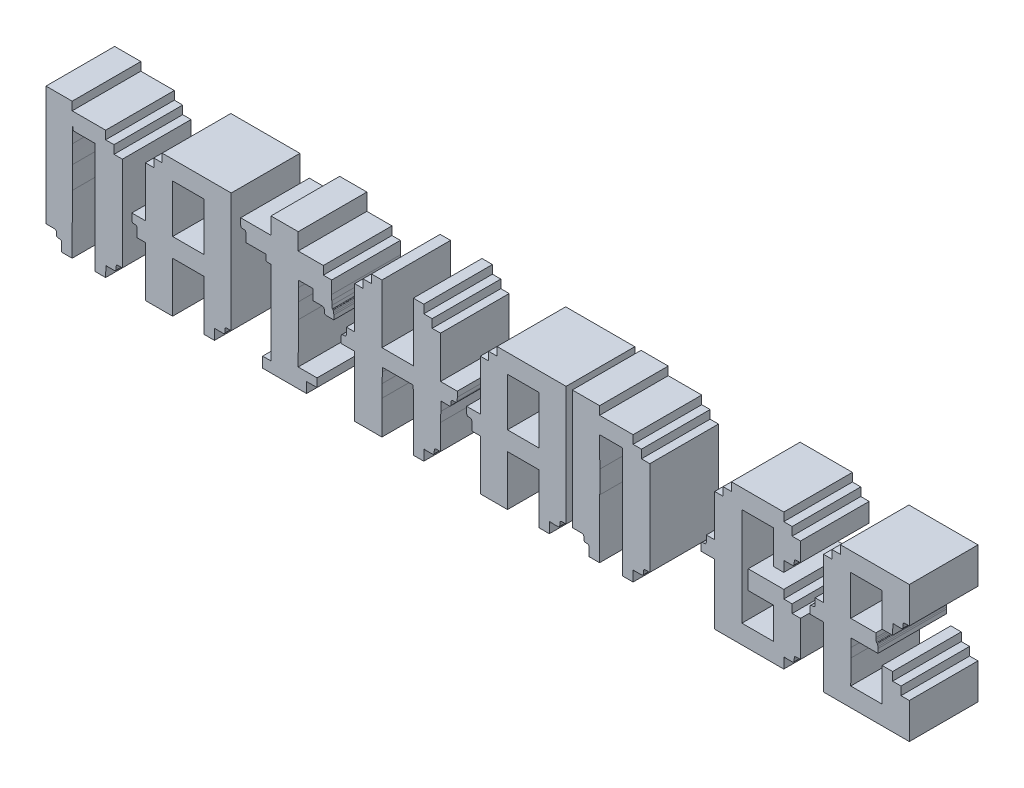
SolidWorks part; units mm, degrees
ref_plane "Front Plane" through (0, 0, 0) normal (0, 0, 1) x (1, 0, 0)
ref_plane "Top Plane" through (0, 0, 0) normal (0, 1, 0) x (1, 0, 0)
ref_plane "Right Plane" through (0, 0, 0) normal (1, 0, 0) x (0, 0, -1)
sketch "Model" plane through (0, 0, 0) normal (0, 0, 1) x (1, 0, 0)
  line L0 (0, 2235.2) -> (0, 787.4)
  line L1 (0, 787.4) -> (127, 787.4)
  line L2 (381, 508) -> (381, 381)
  line L3 (381, 381) -> (508, 381)
  line L4 (508, 381) -> (635, 381)
  line L5 (635, 381) -> (639.0649, 1809.75)
  line L6 (653.3743, 3155.95) -> (663.6186, 3073.4)
  line L7 (663.6186, 3073.4) -> (928.7093, 3073.4)
  line L8 (928.7093, 3073.4) -> (1193.8, 3073.4)
  line L9 (1193.8, 3073.4) -> (1193.8, 1727.2)
  line L10 (1193.8, 1727.2) -> (1193.8, 381)
  line L11 (1193.8, 381) -> (1320.8, 381)
  line L12 (1320.8, 381) -> (1447.8, 381)
  line L13 (1447.8, 381) -> (1451.8649, 590.55)
  line L14 (1778, 787.4) -> (1854.2, 787.4)
  line L15 (1854.2, 787.4) -> (1854.2, 1930.4)
  line L16 (1854.2, 1930.4) -> (1854.2, 3073.4)
  line L17 (1854.2, 3073.4) -> (1752.6, 3073.4)
  line L18 (1752.6, 3073.4) -> (1651, 3073.4)
  line L19 (1651, 3073.4) -> (1651, 3175)
  line L20 (1651, 3175) -> (1651, 3276.6)
  line L21 (1651, 3276.6) -> (1549.4, 3276.6)
  line L22 (1549.4, 3276.6) -> (1447.8, 3276.6)
  line L23 (1447.8, 3276.6) -> (1447.8, 3378.2)
  line L24 (1447.8, 3378.2) -> (1447.8, 3479.8)
  line L25 (1447.8, 3479.8) -> (1041.4, 3479.8)
  line L26 (1041.4, 3479.8) -> (635, 3479.8)
  line L27 (635, 3479.8) -> (635, 3581.4)
  line L28 (635, 3581.4) -> (635, 3683)
  line L29 (635, 3683) -> (317.5, 3683)
  line L30 (317.5, 3683) -> (0, 3683)
  line L31 (0, 3683) -> (0, 2235.2)
  line L32 (2819.4, 3581.4) -> (2819.4, 3479.8)
  line L33 (2819.4, 3479.8) -> (2717.8, 3479.8)
  line L34 (2717.8, 3479.8) -> (2616.2, 3479.8)
  line L35 (2616.2, 3479.8) -> (2616.2, 3378.2)
  line L36 (2616.2, 3378.2) -> (2616.2, 3276.6)
  line L37 (2616.2, 3276.6) -> (2514.6, 3276.6)
  line L38 (2514.6, 3276.6) -> (2413, 3276.6)
  line L39 (2413, 3276.6) -> (2413, 2667)
  line L40 (2413, 2667) -> (2413, 2057.4)
  line L41 (2413, 2057.4) -> (2247.9, 2057.4)
  line L42 (2247.9, 2057.4) -> (2082.8, 2057.4)
  line L43 (2082.8, 2057.4) -> (2082.8, 1955.8)
  line L44 (2209.8, 1727.2) -> (2209.8, 1600.2)
  line L45 (2209.8, 1600.2) -> (2311.4, 1600.2)
  line L46 (2311.4, 1600.2) -> (2413, 1600.2)
  line L47 (2413, 1600.2) -> (2413, 990.6)
  line L48 (2413, 990.6) -> (2413, 381)
  line L49 (2413, 381) -> (2743.2, 381)
  line L50 (2743.2, 381) -> (3073.4, 381)
  line L51 (3073.4, 381) -> (3073.4, 990.6)
  line L52 (3073.4, 990.6) -> (3073.4, 1600.2)
  line L53 (3073.4, 1600.2) -> (3454.4, 1600.2)
  line L54 (3454.4, 1600.2) -> (3835.4, 1600.2)
  line L55 (3835.4, 1600.2) -> (3835.4, 990.6)
  line L56 (3835.4, 990.6) -> (3835.4, 381)
  line L57 (3835.4, 381) -> (3962.4, 381)
  line L58 (3962.4, 381) -> (4089.4, 381)
  line L59 (4089.4, 381) -> (4093.4649, 590.55)
  line L60 (4419.6, 787.4) -> (4495.8, 787.4)
  line L61 (4495.8, 787.4) -> (4495.8, 2235.2)
  line L62 (4495.8, 2235.2) -> (4495.8, 3683)
  line L63 (4495.8, 3683) -> (3657.6, 3683)
  line L64 (3657.6, 3683) -> (2819.4, 3683)
  line L65 (2819.4, 3683) -> (2819.4, 3581.4)
  line L66 (3835.4, 2641.6) -> (3835.4, 2057.4)
  line L67 (3835.4, 2057.4) -> (3454.4, 2057.4)
  line L68 (3454.4, 2057.4) -> (3073.4, 2057.4)
  line L69 (3073.4, 2057.4) -> (3073.4, 2641.6)
  line L70 (3073.4, 2641.6) -> (3073.4, 3225.8)
  line L71 (3073.4, 3225.8) -> (3454.4, 3225.8)
  line L72 (3454.4, 3225.8) -> (3835.4, 3225.8)
  line L73 (3835.4, 3225.8) -> (3835.4, 2641.6)
  line L74 (5461, 3479.8) -> (5461, 3276.6)
  line L75 (5461, 3276.6) -> (5092.7, 3276.6)
  line L76 (5092.7, 3276.6) -> (4724.4, 3276.6)
  line L77 (4724.4, 3276.6) -> (4724.4, 3175)
  line L78 (4851.4, 2946.4) -> (4851.4, 2819.4)
  line L79 (4851.4, 2819.4) -> (5092.7, 2819.4)
  line L80 (5092.7, 2819.4) -> (5334, 2819.4)
  line L81 (5334, 2819.4) -> (5334, 2743.2)
  line L82 (5397.5, 2667) -> (5461, 2667)
  line L83 (5461, 2667) -> (5461, 1651)
  line L84 (5461, 1651) -> (5461, 635)
  line L85 (5461, 635) -> (5359.4, 635)
  line L86 (5359.4, 635) -> (5257.8, 635)
  line L87 (5257.8, 635) -> (5257.8, 508)
  line L88 (5257.8, 508) -> (5257.8, 381)
  line L89 (5257.8, 381) -> (5791.2, 381)
  line L90 (5791.2, 381) -> (6324.6, 381)
  line L91 (6324.6, 381) -> (6324.6, 609.6)
  line L92 (6324.6, 609.6) -> (6324.6, 838.2)
  line L93 (6324.6, 838.2) -> (6223, 838.2)
  line L94 (6223, 838.2) -> (6121.4, 838.2)
  line L95 (6121.4, 838.2) -> (6125.4649, 1835.15)
  line L96 (6139.7743, 2749.55) -> (6150.0186, 2667)
  line L97 (6150.0186, 2667) -> (6313.5093, 2667)
  line L98 (6313.5093, 2667) -> (6477, 2667)
  line L99 (6477, 2667) -> (6477, 2540)
  line L100 (6477, 2540) -> (6477, 2413)
  line L101 (6477, 2413) -> (6616.7, 2413)
  line L102 (6870.7, 2260.6) -> (6985, 2260.6)
  line L103 (6985, 2260.6) -> (6985, 2362.2)
  line L104 (6934.2, 2768.6) -> (6934.2, 3073.4)
  line L105 (6934.2, 3073.4) -> (6832.6, 3073.4)
  line L106 (6832.6, 3073.4) -> (6731, 3073.4)
  line L107 (6731, 3073.4) -> (6731, 3175)
  line L108 (6731, 3175) -> (6731, 3276.6)
  line L109 (6731, 3276.6) -> (6426.2, 3276.6)
  line L110 (6426.2, 3276.6) -> (6121.4, 3276.6)
  line L111 (6121.4, 3276.6) -> (6121.4, 3479.8)
  line L112 (6121.4, 3479.8) -> (6121.4, 3683)
  line L113 (6121.4, 3683) -> (5791.2, 3683)
  line L114 (5791.2, 3683) -> (5461, 3683)
  line L115 (5461, 3683) -> (5461, 3479.8)
  line L116 (7899.4, 3581.4) -> (7899.4, 3479.8)
  line L117 (7899.4, 3479.8) -> (7797.8, 3479.8)
  line L118 (7797.8, 3479.8) -> (7696.2, 3479.8)
  line L119 (7696.2, 3479.8) -> (7696.2, 3378.2)
  line L120 (7696.2, 3378.2) -> (7696.2, 3276.6)
  line L121 (7696.2, 3276.6) -> (7594.6, 3276.6)
  line L122 (7594.6, 3276.6) -> (7493, 3276.6)
  line L123 (7493, 3276.6) -> (7493, 2768.6)
  line L124 (7493, 2768.6) -> (7493, 2260.6)
  line L125 (7493, 2260.6) -> (7391.4, 2260.6)
  line L126 (7391.4, 2260.6) -> (7289.8, 2260.6)
  line L127 (7289.8, 2260.6) -> (7289.8, 2159)
  line L128 (7162.8, 1955.8) -> (7162.8, 1854.2)
  line L129 (7162.8, 1854.2) -> (7327.9, 1854.2)
  line L130 (7327.9, 1854.2) -> (7493, 1854.2)
  line L131 (7493, 1854.2) -> (7493, 1117.6)
  line L132 (7493, 1117.6) -> (7493, 381)
  line L133 (7493, 381) -> (7823.2, 381)
  line L134 (7823.2, 381) -> (8153.4, 381)
  line L135 (8153.4, 381) -> (8157.4649, 1200.15)
  line L136 (8171.7743, 1936.75) -> (8182.0186, 1854.2)
  line L137 (8182.0186, 1854.2) -> (8497.9093, 1854.2)
  line L138 (8497.9093, 1854.2) -> (8813.8, 1854.2)
  line L139 (8813.8, 1854.2) -> (8813.8, 1930.4)
  line L140 (8915.4, 1193.8) -> (8915.4, 381)
  line L141 (8915.4, 381) -> (9042.4, 381)
  line L142 (9042.4, 381) -> (9169.4, 381)
  line L143 (9169.4, 381) -> (9173.4649, 590.55)
  line L144 (9499.6, 787.4) -> (9575.8, 787.4)
  line L145 (9575.8, 787.4) -> (9579.8649, 1403.35)
  line L146 (9982.2, 2133.6) -> (9982.2, 2260.6)
  line L147 (9982.2, 2260.6) -> (9779, 2260.6)
  line L148 (9779, 2260.6) -> (9575.8, 2260.6)
  line L149 (9575.8, 2260.6) -> (9575.8, 2768.6)
  line L150 (9575.8, 2768.6) -> (9575.8, 3276.6)
  line L151 (9575.8, 3276.6) -> (9474.2, 3276.6)
  line L152 (9474.2, 3276.6) -> (9372.6, 3276.6)
  line L153 (9372.6, 3276.6) -> (9372.6, 3378.2)
  line L154 (9372.6, 3378.2) -> (9372.6, 3479.8)
  line L155 (9372.6, 3479.8) -> (9271, 3479.8)
  line L156 (9271, 3479.8) -> (9169.4, 3479.8)
  line L157 (9169.4, 3479.8) -> (9169.4, 3581.4)
  line L158 (9169.4, 3581.4) -> (9169.4, 3683)
  line L159 (9169.4, 3683) -> (9042.4, 3683)
  line L160 (9042.4, 3683) -> (8915.4, 3683)
  line L161 (8915.4, 3683) -> (8915.4, 2971.8)
  line L162 (8915.4, 2971.8) -> (8915.4, 2260.6)
  line L163 (8915.4, 2260.6) -> (8534.4, 2260.6)
  line L164 (8534.4, 2260.6) -> (8153.4, 2260.6)
  line L165 (8153.4, 2260.6) -> (8153.4, 2971.8)
  line L166 (8153.4, 2971.8) -> (8153.4, 3683)
  line L167 (8153.4, 3683) -> (8026.4, 3683)
  line L168 (8026.4, 3683) -> (7899.4, 3683)
  line L169 (7899.4, 3683) -> (7899.4, 3581.4)
  line L170 (10947.4, 3581.4) -> (10947.4, 3479.8)
  line L171 (10947.4, 3479.8) -> (10845.8, 3479.8)
  line L172 (10845.8, 3479.8) -> (10744.2, 3479.8)
  line L173 (10744.2, 3479.8) -> (10744.2, 3378.2)
  line L174 (10744.2, 3378.2) -> (10744.2, 3276.6)
  line L175 (10744.2, 3276.6) -> (10642.6, 3276.6)
  line L176 (10642.6, 3276.6) -> (10541, 3276.6)
  line L177 (10541, 3276.6) -> (10541, 2667)
  line L178 (10541, 2667) -> (10541, 2057.4)
  line L179 (10541, 2057.4) -> (10375.9, 2057.4)
  line L180 (10375.9, 2057.4) -> (10210.8, 2057.4)
  line L181 (10210.8, 2057.4) -> (10210.8, 1955.8)
  line L182 (10337.8, 1727.2) -> (10337.8, 1600.2)
  line L183 (10337.8, 1600.2) -> (10439.4, 1600.2)
  line L184 (10439.4, 1600.2) -> (10541, 1600.2)
  line L185 (10541, 1600.2) -> (10541, 990.6)
  line L186 (10541, 990.6) -> (10541, 381)
  line L187 (10541, 381) -> (10871.2, 381)
  line L188 (10871.2, 381) -> (11201.4, 381)
  line L189 (11201.4, 381) -> (11201.4, 990.6)
  line L190 (11201.4, 990.6) -> (11201.4, 1600.2)
  line L191 (11201.4, 1600.2) -> (11582.4, 1600.2)
  line L192 (11582.4, 1600.2) -> (11963.4, 1600.2)
  line L193 (11963.4, 1600.2) -> (11963.4, 990.6)
  line L194 (11963.4, 990.6) -> (11963.4, 381)
  line L195 (11963.4, 381) -> (12090.4, 381)
  line L196 (12090.4, 381) -> (12217.4, 381)
  line L197 (12217.4, 381) -> (12221.4649, 590.55)
  line L198 (12547.6, 787.4) -> (12623.8, 787.4)
  line L199 (12623.8, 787.4) -> (12623.8, 2235.2)
  line L200 (12623.8, 2235.2) -> (12623.8, 3683)
  line L201 (12623.8, 3683) -> (11785.6, 3683)
  line L202 (11785.6, 3683) -> (10947.4, 3683)
  line L203 (10947.4, 3683) -> (10947.4, 3581.4)
  line L204 (11963.4, 2641.6) -> (11963.4, 2057.4)
  line L205 (11963.4, 2057.4) -> (11582.4, 2057.4)
  line L206 (11582.4, 2057.4) -> (11201.4, 2057.4)
  line L207 (11201.4, 2057.4) -> (11201.4, 2641.6)
  line L208 (11201.4, 2641.6) -> (11201.4, 3225.8)
  line L209 (11201.4, 3225.8) -> (11582.4, 3225.8)
  line L210 (11582.4, 3225.8) -> (11963.4, 3225.8)
  line L211 (11963.4, 3225.8) -> (11963.4, 2641.6)
  line L212 (12776.2, 2235.2) -> (12776.2, 787.4)
  line L213 (12776.2, 787.4) -> (12915.9, 787.4)
  line L214 (13182.6, 508) -> (13182.6, 381)
  line L215 (13182.6, 381) -> (13309.6, 381)
  line L216 (13309.6, 381) -> (13436.6, 381)
  line L217 (13436.6, 381) -> (13440.6649, 1809.75)
  line L218 (13454.9743, 3155.95) -> (13465.2186, 3073.4)
  line L219 (13465.2186, 3073.4) -> (13730.3093, 3073.4)
  line L220 (13730.3093, 3073.4) -> (13995.4, 3073.4)
  line L221 (13995.4, 3073.4) -> (13995.4, 1727.2)
  line L222 (13995.4, 1727.2) -> (13995.4, 381)
  line L223 (13995.4, 381) -> (14122.4, 381)
  line L224 (14122.4, 381) -> (14249.4, 381)
  line L225 (14249.4, 381) -> (14253.4649, 590.55)
  line L226 (14579.6, 787.4) -> (14655.8, 787.4)
  line L227 (14655.8, 787.4) -> (14655.8, 1930.4)
  line L228 (14655.8, 1930.4) -> (14655.8, 3073.4)
  line L229 (14655.8, 3073.4) -> (14554.2, 3073.4)
  line L230 (14554.2, 3073.4) -> (14452.6, 3073.4)
  line L231 (14452.6, 3073.4) -> (14452.6, 3175)
  line L232 (14452.6, 3175) -> (14452.6, 3276.6)
  line L233 (14452.6, 3276.6) -> (14351, 3276.6)
  line L234 (14351, 3276.6) -> (14249.4, 3276.6)
  line L235 (14249.4, 3276.6) -> (14249.4, 3378.2)
  line L236 (14249.4, 3378.2) -> (14249.4, 3479.8)
  line L237 (14249.4, 3479.8) -> (13843, 3479.8)
  line L238 (13843, 3479.8) -> (13436.6, 3479.8)
  line L239 (13436.6, 3479.8) -> (13436.6, 3581.4)
  line L240 (13436.6, 3581.4) -> (13436.6, 3683)
  line L241 (13436.6, 3683) -> (13106.4, 3683)
  line L242 (13106.4, 3683) -> (12776.2, 3683)
  line L243 (12776.2, 3683) -> (12776.2, 2235.2)
  line L244 (16637, 3581.4) -> (16637, 3479.8)
  line L245 (16637, 3479.8) -> (16535.4, 3479.8)
  line L246 (16535.4, 3479.8) -> (16433.8, 3479.8)
  line L247 (16433.8, 3479.8) -> (16433.8, 3378.2)
  line L248 (16433.8, 3378.2) -> (16433.8, 3276.6)
  line L249 (16433.8, 3276.6) -> (16332.2, 3276.6)
  line L250 (16332.2, 3276.6) -> (16230.6, 3276.6)
  line L251 (16230.6, 3276.6) -> (16230.6, 2768.6)
  line L252 (16230.6, 2768.6) -> (16230.6, 2260.6)
  line L253 (16230.6, 2260.6) -> (16129, 2260.6)
  line L254 (16129, 2260.6) -> (16027.4, 2260.6)
  line L255 (16027.4, 2260.6) -> (16027.4, 2159)
  line L256 (15900.4, 1955.8) -> (15900.4, 1854.2)
  line L257 (15900.4, 1854.2) -> (16065.5, 1854.2)
  line L258 (16065.5, 1854.2) -> (16230.6, 1854.2)
  line L259 (16230.6, 1854.2) -> (16230.6, 1117.6)
  line L260 (16230.6, 1117.6) -> (16230.6, 381)
  line L261 (16230.6, 381) -> (17068.8, 381)
  line L262 (17068.8, 381) -> (17907, 381)
  line L263 (17907, 381) -> (17911.0649, 590.55)
  line L264 (18237.2, 787.4) -> (18313.4, 787.4)
  line L265 (18313.4, 787.4) -> (18313.4, 1219.2)
  line L266 (18313.4, 1219.2) -> (18313.4, 1651)
  line L267 (18313.4, 1651) -> (18211.8, 1651)
  line L268 (18211.8, 1651) -> (18110.2, 1651)
  line L269 (18110.2, 1651) -> (18110.2, 1752.6)
  line L270 (18110.2, 1752.6) -> (18110.2, 1854.2)
  line L271 (18110.2, 1854.2) -> (18008.6, 1854.2)
  line L272 (18008.6, 1854.2) -> (17907, 1854.2)
  line L273 (17907, 1854.2) -> (17907, 1955.8)
  line L274 (17907, 1955.8) -> (17907, 2057.4)
  line L275 (17907, 2057.4) -> (17475.2, 2057.4)
  line L276 (17475.2, 2057.4) -> (17043.4, 2057.4)
  line L277 (17043.4, 2057.4) -> (17043.4, 1828.8)
  line L278 (17043.4, 1828.8) -> (17043.4, 1600.2)
  line L279 (17043.4, 1600.2) -> (17348.2, 1600.2)
  line L280 (17348.2, 1600.2) -> (17653, 1600.2)
  line L281 (17653, 1600.2) -> (17653, 1219.2)
  line L282 (17653, 1219.2) -> (17653, 838.2)
  line L283 (17653, 838.2) -> (17272, 838.2)
  line L284 (17272, 838.2) -> (16891, 838.2)
  line L285 (16891, 838.2) -> (16891, 2032)
  line L286 (16891, 2032) -> (16891, 3225.8)
  line L287 (16891, 3225.8) -> (17272, 3225.8)
  line L288 (17272, 3225.8) -> (17653, 3225.8)
  line L289 (17653, 3225.8) -> (17653, 2819.4)
  line L290 (17653, 2819.4) -> (17653, 2413)
  line L291 (17653, 2413) -> (17780, 2413)
  line L292 (17780, 2413) -> (17907, 2413)
  line L293 (17907, 2413) -> (17911.0649, 2622.55)
  line L294 (18237.2, 2819.4) -> (18313.4, 2819.4)
  line L295 (18313.4, 2819.4) -> (18313.4, 3048)
  line L296 (18313.4, 3048) -> (18313.4, 3276.6)
  line L297 (18313.4, 3276.6) -> (18211.8, 3276.6)
  line L298 (18211.8, 3276.6) -> (18110.2, 3276.6)
  line L299 (18110.2, 3276.6) -> (18110.2, 3378.2)
  line L300 (18110.2, 3378.2) -> (18110.2, 3479.8)
  line L301 (18110.2, 3479.8) -> (18008.6, 3479.8)
  line L302 (18008.6, 3479.8) -> (17907, 3479.8)
  line L303 (17907, 3479.8) -> (17907, 3581.4)
  line L304 (17907, 3581.4) -> (17907, 3683)
  line L305 (17907, 3683) -> (17272, 3683)
  line L306 (17272, 3683) -> (16637, 3683)
  line L307 (16637, 3683) -> (16637, 3581.4)
  line L308 (19278.6, 3581.4) -> (19278.6, 3479.8)
  line L309 (19278.6, 3479.8) -> (19177, 3479.8)
  line L310 (19177, 3479.8) -> (19075.4, 3479.8)
  line L311 (19075.4, 3479.8) -> (19075.4, 3378.2)
  line L312 (19075.4, 3378.2) -> (19075.4, 3276.6)
  line L313 (19075.4, 3276.6) -> (18973.8, 3276.6)
  line L314 (18973.8, 3276.6) -> (18872.2, 3276.6)
  line L315 (18872.2, 3276.6) -> (18872.2, 2768.6)
  line L316 (18872.2, 2768.6) -> (18872.2, 2260.6)
  line L317 (18872.2, 2260.6) -> (18770.6, 2260.6)
  line L318 (18770.6, 2260.6) -> (18669, 2260.6)
  line L319 (18669, 2260.6) -> (18669, 2159)
  line L320 (18542, 1955.8) -> (18542, 1854.2)
  line L321 (18542, 1854.2) -> (18707.1, 1854.2)
  line L322 (18707.1, 1854.2) -> (18872.2, 1854.2)
  line L323 (18872.2, 1854.2) -> (18872.2, 1117.6)
  line L324 (18872.2, 1117.6) -> (18872.2, 381)
  line L325 (18872.2, 381) -> (19913.6, 381)
  line L326 (19913.6, 381) -> (20955, 381)
  line L327 (20955, 381) -> (20955, 812.8)
  line L328 (20955, 812.8) -> (20955, 1244.6)
  line L329 (20955, 1244.6) -> (20853.4, 1244.6)
  line L330 (20853.4, 1244.6) -> (20751.8, 1244.6)
  line L331 (20751.8, 1244.6) -> (20751.8, 1346.2)
  line L332 (20751.8, 1346.2) -> (20751.8, 1447.8)
  line L333 (20751.8, 1447.8) -> (20650.2, 1447.8)
  line L334 (20650.2, 1447.8) -> (20548.6, 1447.8)
  line L335 (20548.6, 1447.8) -> (20548.6, 1549.4)
  line L336 (20548.6, 1549.4) -> (20548.6, 1651)
  line L337 (20548.6, 1651) -> (20421.6, 1651)
  line L338 (20421.6, 1651) -> (20294.6, 1651)
  line L339 (20294.6, 1651) -> (20294.6, 1244.6)
  line L340 (20294.6, 1244.6) -> (20294.6, 838.2)
  line L341 (20294.6, 838.2) -> (19913.6, 838.2)
  line L342 (19913.6, 838.2) -> (19532.6, 838.2)
  line L343 (19532.6, 838.2) -> (19536.6649, 1428.75)
  line L344 (19550.9743, 1936.75) -> (19561.2186, 1854.2)
  line L345 (19561.2186, 1854.2) -> (19877.1093, 1854.2)
  line L346 (19877.1093, 1854.2) -> (20193, 1854.2)
  line L347 (20193, 1854.2) -> (20193, 1955.8)
  line L348 (20142.2, 2159) -> (20142.2, 2260.6)
  line L349 (20142.2, 2260.6) -> (19837.4, 2260.6)
  line L350 (19837.4, 2260.6) -> (19532.6, 2260.6)
  line L351 (19532.6, 2260.6) -> (19532.6, 2743.2)
  line L352 (19532.6, 2743.2) -> (19532.6, 3225.8)
  line L353 (19532.6, 3225.8) -> (19913.6, 3225.8)
  line L354 (19913.6, 3225.8) -> (20294.6, 3225.8)
  line L355 (20294.6, 3225.8) -> (20294.6, 2819.4)
  line L356 (20294.6, 2819.4) -> (20294.6, 2413)
  line L357 (20294.6, 2413) -> (20421.6, 2413)
  line L358 (20421.6, 2413) -> (20548.6, 2413)
  line L359 (20548.6, 2413) -> (20552.6649, 2622.55)
  line L360 (20878.8, 2819.4) -> (20955, 2819.4)
  line L361 (20955, 2819.4) -> (20955, 3251.2)
  line L362 (20955, 3251.2) -> (20955, 3683)
  line L363 (20955, 3683) -> (20116.8, 3683)
  line L364 (20116.8, 3683) -> (19278.6, 3683)
  line L365 (19278.6, 3683) -> (19278.6, 3581.4)
  line L366 (6350, 736.6) -> (6350, 635)
  line L367 (6350, 635) -> (6464.3, 635)
  line L368 (6464.3, 635) -> (6578.6, 635)
  line L369 (6578.6, 635) -> (6578.6, 736.6)
  line L370 (6578.6, 736.6) -> (6578.6, 838.2)
  line L371 (6578.6, 838.2) -> (6464.3, 838.2)
  line L372 (6464.3, 838.2) -> (6350, 838.2)
  line L373 (6350, 838.2) -> (6350, 736.6)
  arc A0 (208.2797, 785.8195) -> (127, 787.4) centre (127.0016, -1303.2891) ccw
  arc A1 (237.0667, 777.24) -> (208.2797, 785.8195) centre (205.9268, 725.3402) ccw
  arc A2 (250.4181, 757.4088) -> (237.0667, 777.24) centre (222.5611, 753.064) ccw
  arc A3 (254, 711.2) -> (250.4181, 757.4088) centre (-45.8505, 711.2001) ccw
  arc A4 (254, 711.2) -> (256.4698, 670.2146) centre (595.3029, 711.1997) ccw
  arc A5 (256.4698, 670.2146) -> (265.6417, 648.97) centre (297.0213, 675.1196) ccw
  arc A6 (265.6417, 648.97) -> (283.8593, 638.2149) centre (289.8205, 669.119) ccw
  arc A7 (283.8593, 638.2149) -> (317.5, 635) centre (317.4999, 812.6129) ccw
  arc A8 (353.5642, 630.4259) -> (317.5, 635) centre (317.4999, 490.54) ccw
  arc A9 (371.475, 615.95) -> (353.5642, 630.4259) centre (346.6294, 603.5272) ccw
  arc A10 (379.4056, 585.2081) -> (371.475, 615.95) centre (303.7388, 582.0818) ccw
  arc A11 (381, 508) -> (379.4056, 585.2081) centre (-1489.2251, 508.0001) ccw
  arc A12 (641.3546, 2352.0677) -> (639.0649, 1809.75) centre (197703.2292, 1248.8931) ccw
  arc A13 (644.9451, 2794.5556) -> (641.3546, 2352.0677) centre (88647.772, 1859.2232) ccw
  arc A14 (649.1502, 3155.7157) -> (644.9451, 2794.5556) centre (178733.8415, 901.5919) ccw
  arc A15 (653.3743, 3155.95) -> (649.1502, 3155.7157) centre (651.2702, 3155.6889) ccw
  arc A16 (1454.0941, 666.2478) -> (1451.8649, 590.55) centre (5221.1922, 517.4322) ccw
  arc A17 (1457.7451, 714.2956) -> (1454.0941, 666.2478) centre (2116.389, 640.0848) ccw
  arc A18 (1461.9584, 719.9691) -> (1457.7451, 714.2956) centre (1464.7316, 713.5085) ccw
  arc A19 (1466.1743, 717.55) -> (1461.9584, 719.9691) centre (1463.1575, 717.1756) ccw
  arc A20 (1466.1743, 717.55) -> (1475.5882, 668.0537) centre (1854.1503, 765.6976) ccw
  arc A21 (1475.5882, 668.0537) -> (1490.7882, 646.5789) centre (1511.4135, 677.2943) ccw
  arc A22 (1490.7882, 646.5789) -> (1519.1857, 637.0232) centre (1522.472, 693.7629) ccw
  arc A23 (1519.1857, 637.0232) -> (1589.1093, 635) centre (1589.11, 1844.3388) ccw
  arc A24 (1589.1093, 635) -> (1659.4708, 636.7636) centre (1589.1086, 2039.5227) ccw
  arc A25 (1659.4708, 636.7636) -> (1686.0591, 645.6438) centre (1656.8593, 688.827) ccw
  arc A26 (1686.0591, 645.6438) -> (1698.517, 665.5205) centre (1669.8145, 669.6676) ccw
  arc A27 (1698.517, 665.5205) -> (1701.8, 711.2) centre (1382.3684, 711.1999) ccw
  arc A28 (1704.4377, 754.087) -> (1701.8, 711.2) centre (2051.7703, 711.2003) ccw
  arc A29 (1714.5, 774.7) -> (1704.4377, 754.087) centre (1739.4342, 749.7658) ccw
  arc A30 (1735.113, 784.7623) -> (1714.5, 774.7) centre (1739.4342, 749.7658) ccw
  arc A31 (1778, 787.4) -> (1735.113, 784.7623) centre (1777.9997, 437.4297) ccw
  arc A32 (2082.8, 1955.8) -> (2084.705, 1896.8328) centre (2996.3762, 1955.7993) ccw
  arc A33 (2084.705, 1896.8328) -> (2093.1188, 1870.71) centre (2140.7112, 1900.4552) ccw
  arc A34 (2093.1188, 1870.71) -> (2111.0355, 1858.0546) centre (2117.1601, 1885.7359) ccw
  arc A35 (2111.0355, 1858.0546) -> (2146.3, 1854.2) centre (2146.3001, 2017.4403) ccw
  arc A36 (2182.3642, 1849.6259) -> (2146.3, 1854.2) centre (2146.2999, 1709.74) ccw
  arc A37 (2200.275, 1835.15) -> (2182.3642, 1849.6259) centre (2175.4294, 1822.7272) ccw
  arc A38 (2208.2056, 1804.4081) -> (2200.275, 1835.15) centre (2132.5388, 1801.2818) ccw
  arc A39 (2209.8, 1727.2) -> (2208.2056, 1804.4081) centre (339.5749, 1727.2001) ccw
  arc A40 (4095.6941, 666.2478) -> (4093.4649, 590.55) centre (7862.7922, 517.4322) ccw
  arc A41 (4099.3451, 714.2956) -> (4095.6941, 666.2478) centre (4757.989, 640.0848) ccw
  arc A42 (4103.5584, 719.9691) -> (4099.3451, 714.2956) centre (4106.3316, 713.5085) ccw
  arc A43 (4107.7743, 717.55) -> (4103.5584, 719.9691) centre (4104.7575, 717.1756) ccw
  arc A44 (4107.7743, 717.55) -> (4117.1882, 668.0537) centre (4495.7503, 765.6976) ccw
  arc A45 (4117.1882, 668.0537) -> (4132.3882, 646.5789) centre (4153.0135, 677.2943) ccw
  arc A46 (4132.3882, 646.5789) -> (4160.7857, 637.0232) centre (4164.072, 693.7629) ccw
  arc A47 (4160.7857, 637.0232) -> (4230.7093, 635) centre (4230.71, 1844.3388) ccw
  arc A48 (4230.7093, 635) -> (4301.0708, 636.7636) centre (4230.7086, 2039.5227) ccw
  arc A49 (4301.0708, 636.7636) -> (4327.6591, 645.6438) centre (4298.4593, 688.827) ccw
  arc A50 (4327.6591, 645.6438) -> (4340.117, 665.5205) centre (4311.4145, 669.6676) ccw
  arc A51 (4340.117, 665.5205) -> (4343.4, 711.2) centre (4023.9684, 711.1999) ccw
  arc A52 (4346.0377, 754.087) -> (4343.4, 711.2) centre (4693.3703, 711.2003) ccw
  arc A53 (4356.1, 774.7) -> (4346.0377, 754.087) centre (4381.0342, 749.7658) ccw
  arc A54 (4376.713, 784.7623) -> (4356.1, 774.7) centre (4381.0342, 749.7658) ccw
  arc A55 (4419.6, 787.4) -> (4376.713, 784.7623) centre (4419.5997, 437.4297) ccw
  arc A56 (4724.4, 3175) -> (4726.305, 3116.0328) centre (5637.9762, 3174.9993) ccw
  arc A57 (4726.305, 3116.0328) -> (4734.7188, 3089.91) centre (4782.3112, 3119.6552) ccw
  arc A58 (4734.7188, 3089.91) -> (4752.6355, 3077.2546) centre (4758.7601, 3104.9359) ccw
  arc A59 (4752.6355, 3077.2546) -> (4787.9, 3073.4) centre (4787.9001, 3236.6403) ccw
  arc A60 (4823.9642, 3068.8259) -> (4787.9, 3073.4) centre (4787.8999, 2928.94) ccw
  arc A61 (4841.875, 3054.35) -> (4823.9642, 3068.8259) centre (4817.0294, 3041.9272) ccw
  arc A62 (4849.8056, 3023.6081) -> (4841.875, 3054.35) centre (4774.1388, 3020.4818) ccw
  arc A63 (4851.4, 2946.4) -> (4849.8056, 3023.6081) centre (2981.1749, 2946.4001) ccw
  arc A64 (5334, 2743.2) -> (5336.4698, 2702.2146) centre (5675.3029, 2743.1997) ccw
  arc A65 (5336.4698, 2702.2146) -> (5345.6417, 2680.97) centre (5377.0213, 2707.1196) ccw
  arc A66 (5345.6417, 2680.97) -> (5363.8593, 2670.2149) centre (5369.8205, 2701.119) ccw
  arc A67 (5363.8593, 2670.2149) -> (5397.5, 2667) centre (5397.4999, 2844.6129) ccw
  arc A68 (6127.7521, 2211.935) -> (6125.4649, 1835.15) centre (100701.0749, 1449.461) ccw
  arc A69 (6131.3451, 2514.9969) -> (6127.7521, 2211.935) centre (46090.0889, 1889.7061) ccw
  arc A70 (6135.551, 2749.3318) -> (6131.3451, 2514.9969) centre (57120.1006, 1717.0416) ccw
  arc A71 (6139.7743, 2749.55) -> (6135.551, 2749.3318) centre (6137.6705, 2749.2889) ccw
  arc A72 (6707.6952, 2411.5437) -> (6616.7, 2413) centre (6616.7014, -430.4361) ccw
  arc A73 (6738.4083, 2403.1864) -> (6707.6952, 2411.5437) centre (6705.4958, 2342.8468) ccw
  arc A74 (6752.5374, 2383.3341) -> (6738.4083, 2403.1864) centre (6725.0758, 2378.7435) ccw
  arc A75 (6756.4, 2336.8) -> (6752.5374, 2383.3341) centre (6474.1649, 2336.8002) ccw
  arc A76 (6756.4, 2336.8) -> (6759.7156, 2291.0503) centre (7073.6908, 2336.7998) ccw
  arc A77 (6759.7156, 2291.0503) -> (6772.275, 2271.1833) centre (6788.296, 2295.2148) ccw
  arc A78 (6772.275, 2271.1833) -> (6799.1127, 2262.3401) centre (6801.689, 2315.3043) ccw
  arc A79 (6799.1127, 2262.3401) -> (6870.7, 2260.6) centre (6870.6997, 3734.0006) ccw
  arc A80 (6985, 2362.2) -> (6983.1613, 2401.1368) centre (6571.8095, 2362.1998) ccw
  arc A81 (6983.1613, 2401.1368) -> (6977.5387, 2433.955) centre (6762.8525, 2380.2834) ccw
  arc A82 (6977.5387, 2433.955) -> (6969.433, 2457.4232) centre (6839.8532, 2399.5335) ccw
  arc A83 (6969.433, 2457.4232) -> (6959.6, 2463.8) centre (6959.6, 2453.0303) ccw
  arc A84 (6948.5244, 2473.6118) -> (6959.6, 2463.8) centre (6959.6, 2474.957) ccw
  arc A85 (6941.0792, 2546.35) -> (6948.5244, 2473.6118) centre (8873.0021, 2707.3453) ccw
  arc A86 (6935.8334, 2642.4702) -> (6941.0792, 2546.35) centre (8617.2439, 2686.0291) ccw
  arc A87 (6934.2, 2768.6) -> (6935.8334, 2642.4702) centre (11804.6888, 2768.6) ccw
  arc A88 (7287.895, 2100.0328) -> (7289.8, 2159) centre (6376.2238, 2158.9993) ccw
  arc A89 (7279.4812, 2073.91) -> (7287.895, 2100.0328) centre (7231.8888, 2103.6552) ccw
  arc A90 (7261.5645, 2061.2546) -> (7279.4812, 2073.91) centre (7255.4399, 2088.9359) ccw
  arc A91 (7226.3, 2057.4) -> (7261.5645, 2061.2546) centre (7226.2999, 2220.6403) ccw
  arc A92 (7226.3, 2057.4) -> (7191.0355, 2053.5454) centre (7226.3001, 1894.1597) ccw
  arc A93 (7191.0355, 2053.5454) -> (7173.1187, 2040.89) centre (7197.1601, 2025.8641) ccw
  arc A94 (7173.1187, 2040.89) -> (7164.705, 2014.7672) centre (7220.7112, 2011.1448) ccw
  arc A95 (7164.705, 2014.7672) -> (7162.8, 1955.8) centre (8076.3762, 1955.8007) ccw
  arc A96 (8159.7501, 1508.7891) -> (8157.4649, 1200.15) centre (71352.4339, 886.5881) ccw
  arc A97 (8163.3451, 1754.4256) -> (8159.7501, 1508.7891) centre (33801.9555, 1256.3471) ccw
  arc A98 (8167.5515, 1936.5457) -> (8163.3451, 1754.4256) centre (32977.3582, 1272.4061) ccw
  arc A99 (8171.7743, 1936.75) -> (8167.5515, 1936.5457) centre (8169.6706, 1936.4889) ccw
  arc A100 (8816.1432, 1968.5233) -> (8813.8, 1930.4) centre (9125.0989, 1930.3998) ccw
  arc A101 (8824.3833, 1990.725) -> (8816.1432, 1968.5233) centre (8867.1218, 1962.2327) ccw
  arc A102 (8839.8269, 2002.5498) -> (8824.3833, 1990.725) centre (8849.4037, 1974.0447) ccw
  arc A103 (8864.6, 2006.6) -> (8839.8269, 2002.5498) centre (8864.5999, 1928.8136) ccw
  arc A104 (8895.2048, 1982.9273) -> (8864.6, 2006.6) centre (8864.6, 1974.9802) ccw
  arc A105 (8908.6531, 1898.65) -> (8895.2048, 1982.9273) centre (8463.5004, 1870.8276) ccw
  arc A106 (8914.4609, 1722.642) -> (8908.6531, 1898.65) centre (5922.5325, 1712.0167) ccw
  arc A107 (8915.4, 1193.8) -> (8914.4609, 1722.642) centre (-139970.6562, 1193.831) ccw
  arc A108 (9175.6941, 666.2478) -> (9173.4649, 590.55) centre (12942.7922, 517.4322) ccw
  arc A109 (9179.3451, 714.2956) -> (9175.6941, 666.2478) centre (9837.989, 640.0848) ccw
  arc A110 (9183.5584, 719.9691) -> (9179.3451, 714.2956) centre (9186.3316, 713.5085) ccw
  arc A111 (9187.7743, 717.55) -> (9183.5584, 719.9691) centre (9184.7575, 717.1756) ccw
  arc A112 (9187.7743, 717.55) -> (9197.1882, 668.0537) centre (9575.7503, 765.6976) ccw
  arc A113 (9197.1882, 668.0537) -> (9212.3882, 646.5789) centre (9233.0135, 677.2943) ccw
  arc A114 (9212.3882, 646.5789) -> (9240.7857, 637.0232) centre (9244.072, 693.7629) ccw
  arc A115 (9240.7857, 637.0232) -> (9310.7093, 635) centre (9310.71, 1844.3388) ccw
  arc A116 (9310.7093, 635) -> (9381.0708, 636.7636) centre (9310.7086, 2039.5227) ccw
  arc A117 (9381.0708, 636.7636) -> (9407.6591, 645.6438) centre (9378.4593, 688.827) ccw
  arc A118 (9407.6591, 645.6438) -> (9420.117, 665.5205) centre (9391.4145, 669.6676) ccw
  arc A119 (9420.117, 665.5205) -> (9423.4, 711.2) centre (9103.9684, 711.1999) ccw
  arc A120 (9426.0377, 754.087) -> (9423.4, 711.2) centre (9773.3703, 711.2003) ccw
  arc A121 (9436.1, 774.7) -> (9426.0377, 754.087) centre (9461.0342, 749.7658) ccw
  arc A122 (9456.713, 784.7623) -> (9436.1, 774.7) centre (9461.0342, 749.7658) ccw
  arc A123 (9499.6, 787.4) -> (9456.713, 784.7623) centre (9499.5997, 437.4297) ccw
  arc A124 (9582.146, 1634.1347) -> (9579.8649, 1403.35) centre (44718.6551, 1171.4385) ccw
  arc A125 (9585.7451, 1814.1156) -> (9582.146, 1634.1347) centre (22767.2757, 1460.5) ccw
  arc A126 (9589.9525, 1936.5777) -> (9585.7451, 1814.1156) centre (17725.8274, 1595.7531) ccw
  arc A127 (9594.1743, 1936.75) -> (9589.9525, 1936.5777) centre (9592.0705, 1936.4889) ccw
  arc A128 (9594.1743, 1936.75) -> (9603.5882, 1887.2537) centre (9982.1503, 1984.8976) ccw
  arc A129 (9603.5882, 1887.2537) -> (9618.7882, 1865.7789) centre (9639.4135, 1896.4943) ccw
  arc A130 (9618.7882, 1865.7789) -> (9647.1857, 1856.2232) centre (9650.472, 1912.9629) ccw
  arc A131 (9647.1857, 1856.2232) -> (9717.1093, 1854.2) centre (9717.11, 3063.5388) ccw
  arc A132 (9717.1093, 1854.2) -> (9787.4708, 1855.9636) centre (9717.1086, 3258.7227) ccw
  arc A133 (9787.4708, 1855.9636) -> (9814.0591, 1864.8438) centre (9784.8593, 1908.027) ccw
  arc A134 (9814.0591, 1864.8438) -> (9826.517, 1884.7205) centre (9797.8145, 1888.8676) ccw
  arc A135 (9826.517, 1884.7205) -> (9829.8, 1930.4) centre (9510.3684, 1930.3999) ccw
  arc A136 (9832.4377, 1973.287) -> (9829.8, 1930.4) centre (10179.7703, 1930.4003) ccw
  arc A137 (9842.5, 1993.9) -> (9832.4377, 1973.287) centre (9867.4342, 1968.9658) ccw
  arc A138 (9863.113, 2003.9623) -> (9842.5, 1993.9) centre (9867.4342, 1968.9658) ccw
  arc A139 (9906, 2006.6) -> (9863.113, 2003.9623) centre (9905.9997, 1656.6297) ccw
  arc A140 (9906, 2006.6) -> (9952.2088, 2010.1819) centre (9906.0001, 2306.4505) ccw
  arc A141 (9952.2088, 2010.1819) -> (9972.04, 2023.5333) centre (9947.864, 2038.0389) ccw
  arc A142 (9972.04, 2023.5333) -> (9980.6195, 2052.3203) centre (9920.1402, 2054.6732) ccw
  arc A143 (9980.6195, 2052.3203) -> (9982.2, 2133.6) centre (7891.5109, 2133.5984) ccw
  arc A144 (10210.8, 1955.8) -> (10212.705, 1896.8328) centre (11124.3762, 1955.7993) ccw
  arc A145 (10212.705, 1896.8328) -> (10221.1187, 1870.71) centre (10268.7112, 1900.4552) ccw
  arc A146 (10221.1187, 1870.71) -> (10239.0355, 1858.0546) centre (10245.1601, 1885.7359) ccw
  arc A147 (10239.0355, 1858.0546) -> (10274.3, 1854.2) centre (10274.3001, 2017.4403) ccw
  arc A148 (10310.3642, 1849.6259) -> (10274.3, 1854.2) centre (10274.2999, 1709.74) ccw
  arc A149 (10328.275, 1835.15) -> (10310.3642, 1849.6259) centre (10303.4294, 1822.7272) ccw
  arc A150 (10336.2056, 1804.4081) -> (10328.275, 1835.15) centre (10260.5388, 1801.2818) ccw
  arc A151 (10337.8, 1727.2) -> (10336.2056, 1804.4081) centre (8467.5749, 1727.2001) ccw
  arc A152 (12223.6941, 666.2478) -> (12221.4649, 590.55) centre (15990.7922, 517.4322) ccw
  arc A153 (12227.3451, 714.2956) -> (12223.6941, 666.2478) centre (12885.989, 640.0848) ccw
  arc A154 (12231.5584, 719.9691) -> (12227.3451, 714.2956) centre (12234.3316, 713.5085) ccw
  arc A155 (12235.7743, 717.55) -> (12231.5584, 719.9691) centre (12232.7575, 717.1756) ccw
  arc A156 (12235.7743, 717.55) -> (12245.1882, 668.0537) centre (12623.7503, 765.6976) ccw
  arc A157 (12245.1882, 668.0537) -> (12260.3882, 646.5789) centre (12281.0135, 677.2943) ccw
  arc A158 (12260.3882, 646.5789) -> (12288.7857, 637.0232) centre (12292.072, 693.7629) ccw
  arc A159 (12288.7857, 637.0232) -> (12358.7093, 635) centre (12358.71, 1844.3388) ccw
  arc A160 (12358.7093, 635) -> (12429.0708, 636.7636) centre (12358.7086, 2039.5227) ccw
  arc A161 (12429.0708, 636.7636) -> (12455.6591, 645.6438) centre (12426.4593, 688.827) ccw
  arc A162 (12455.6591, 645.6438) -> (12468.117, 665.5205) centre (12439.4145, 669.6676) ccw
  arc A163 (12468.117, 665.5205) -> (12471.4, 711.2) centre (12151.9684, 711.1999) ccw
  arc A164 (12474.0377, 754.087) -> (12471.4, 711.2) centre (12821.3703, 711.2003) ccw
  arc A165 (12484.1, 774.7) -> (12474.0377, 754.087) centre (12509.0342, 749.7658) ccw
  arc A166 (12504.713, 784.7623) -> (12484.1, 774.7) centre (12509.0342, 749.7658) ccw
  arc A167 (12547.6, 787.4) -> (12504.713, 784.7623) centre (12547.5997, 437.4297) ccw
  arc A168 (13006.8952, 785.9437) -> (12915.9, 787.4) centre (12915.9014, -2056.0361) ccw
  arc A169 (13037.6083, 777.5864) -> (13006.8952, 785.9437) centre (13004.6958, 717.2468) ccw
  arc A170 (13051.7374, 757.7341) -> (13037.6083, 777.5864) centre (13024.2758, 753.1435) ccw
  arc A171 (13055.6, 711.2) -> (13051.7374, 757.7341) centre (12773.3649, 711.2002) ccw
  arc A172 (13055.6, 711.2) -> (13058.0698, 670.2146) centre (13396.9029, 711.1997) ccw
  arc A173 (13058.0698, 670.2146) -> (13067.2417, 648.97) centre (13098.6213, 675.1196) ccw
  arc A174 (13067.2417, 648.97) -> (13085.4593, 638.2149) centre (13091.4205, 669.119) ccw
  arc A175 (13085.4593, 638.2149) -> (13119.1, 635) centre (13119.0999, 812.6129) ccw
  arc A176 (13155.1642, 630.4259) -> (13119.1, 635) centre (13119.0999, 490.54) ccw
  arc A177 (13173.075, 615.95) -> (13155.1642, 630.4259) centre (13148.2294, 603.5272) ccw
  arc A178 (13181.0056, 585.2081) -> (13173.075, 615.95) centre (13105.3388, 582.0818) ccw
  arc A179 (13182.6, 508) -> (13181.0056, 585.2081) centre (11312.3749, 508.0001) ccw
  arc A180 (13442.9546, 2352.0677) -> (13440.6649, 1809.75) centre (210504.8292, 1248.8931) ccw
  arc A181 (13446.5451, 2794.5556) -> (13442.9546, 2352.0677) centre (101449.372, 1859.2232) ccw
  arc A182 (13450.7502, 3155.7157) -> (13446.5451, 2794.5556) centre (191535.4415, 901.5919) ccw
  arc A183 (13454.9743, 3155.95) -> (13450.7502, 3155.7157) centre (13452.8702, 3155.6889) ccw
  arc A184 (14255.6941, 666.2478) -> (14253.4649, 590.55) centre (18022.7922, 517.4322) ccw
  arc A185 (14259.3451, 714.2956) -> (14255.6941, 666.2478) centre (14917.989, 640.0848) ccw
  arc A186 (14263.5584, 719.9691) -> (14259.3451, 714.2956) centre (14266.3316, 713.5085) ccw
  arc A187 (14267.7743, 717.55) -> (14263.5584, 719.9691) centre (14264.7575, 717.1756) ccw
  arc A188 (14267.7743, 717.55) -> (14277.1882, 668.0537) centre (14655.7503, 765.6976) ccw
  arc A189 (14277.1882, 668.0537) -> (14292.3882, 646.5789) centre (14313.0135, 677.2943) ccw
  arc A190 (14292.3882, 646.5789) -> (14320.7857, 637.0232) centre (14324.072, 693.7629) ccw
  arc A191 (14320.7857, 637.0232) -> (14390.7093, 635) centre (14390.71, 1844.3388) ccw
  arc A192 (14390.7093, 635) -> (14461.0708, 636.7636) centre (14390.7086, 2039.5227) ccw
  arc A193 (14461.0708, 636.7636) -> (14487.6591, 645.6438) centre (14458.4593, 688.827) ccw
  arc A194 (14487.6591, 645.6438) -> (14500.117, 665.5205) centre (14471.4145, 669.6676) ccw
  arc A195 (14500.117, 665.5205) -> (14503.4, 711.2) centre (14183.9684, 711.1999) ccw
  arc A196 (14506.0377, 754.087) -> (14503.4, 711.2) centre (14853.3703, 711.2003) ccw
  arc A197 (14516.1, 774.7) -> (14506.0377, 754.087) centre (14541.0342, 749.7658) ccw
  arc A198 (14536.713, 784.7623) -> (14516.1, 774.7) centre (14541.0342, 749.7658) ccw
  arc A199 (14579.6, 787.4) -> (14536.713, 784.7623) centre (14579.5997, 437.4297) ccw
  arc A200 (16025.495, 2100.0328) -> (16027.4, 2159) centre (15113.8238, 2158.9993) ccw
  arc A201 (16017.0813, 2073.91) -> (16025.495, 2100.0328) centre (15969.4888, 2103.6552) ccw
  arc A202 (15999.1645, 2061.2546) -> (16017.0813, 2073.91) centre (15993.0399, 2088.9359) ccw
  arc A203 (15963.9, 2057.4) -> (15999.1645, 2061.2546) centre (15963.8999, 2220.6403) ccw
  arc A204 (15963.9, 2057.4) -> (15928.6355, 2053.5454) centre (15963.9001, 1894.1597) ccw
  arc A205 (15928.6355, 2053.5454) -> (15910.7188, 2040.89) centre (15934.7601, 2025.8641) ccw
  arc A206 (15910.7188, 2040.89) -> (15902.305, 2014.7672) centre (15958.3112, 2011.1448) ccw
  arc A207 (15902.305, 2014.7672) -> (15900.4, 1955.8) centre (16813.9762, 1955.8007) ccw
  arc A208 (17913.2941, 666.2478) -> (17911.0649, 590.55) centre (21680.3922, 517.4322) ccw
  arc A209 (17916.9451, 714.2956) -> (17913.2941, 666.2478) centre (18575.589, 640.0848) ccw
  arc A210 (17921.1584, 719.9691) -> (17916.9451, 714.2956) centre (17923.9316, 713.5085) ccw
  arc A211 (17925.3743, 717.55) -> (17921.1584, 719.9691) centre (17922.3575, 717.1756) ccw
  arc A212 (17925.3743, 717.55) -> (17934.7882, 668.0537) centre (18313.3503, 765.6976) ccw
  arc A213 (17934.7882, 668.0537) -> (17949.9882, 646.5789) centre (17970.6135, 677.2943) ccw
  arc A214 (17949.9882, 646.5789) -> (17978.3857, 637.0232) centre (17981.672, 693.7629) ccw
  arc A215 (17978.3857, 637.0232) -> (18048.3093, 635) centre (18048.31, 1844.3388) ccw
  arc A216 (18048.3093, 635) -> (18118.6708, 636.7636) centre (18048.3086, 2039.5227) ccw
  arc A217 (18118.6708, 636.7636) -> (18145.2591, 645.6438) centre (18116.0593, 688.827) ccw
  arc A218 (18145.2591, 645.6438) -> (18157.717, 665.5205) centre (18129.0145, 669.6676) ccw
  arc A219 (18157.717, 665.5205) -> (18161, 711.2) centre (17841.5684, 711.1999) ccw
  arc A220 (18163.6377, 754.087) -> (18161, 711.2) centre (18510.9703, 711.2003) ccw
  arc A221 (18173.7, 774.7) -> (18163.6377, 754.087) centre (18198.6342, 749.7658) ccw
  arc A222 (18194.313, 784.7623) -> (18173.7, 774.7) centre (18198.6342, 749.7658) ccw
  arc A223 (18237.2, 787.4) -> (18194.313, 784.7623) centre (18237.1997, 437.4297) ccw
  arc A224 (17913.2941, 2698.2478) -> (17911.0649, 2622.55) centre (21680.3922, 2549.4322) ccw
  arc A225 (17916.9451, 2746.2956) -> (17913.2941, 2698.2478) centre (18575.589, 2672.0848) ccw
  arc A226 (17921.1584, 2751.9691) -> (17916.9451, 2746.2956) centre (17923.9316, 2745.5085) ccw
  arc A227 (17925.3743, 2749.55) -> (17921.1584, 2751.9691) centre (17922.3575, 2749.1756) ccw
  arc A228 (17925.3743, 2749.55) -> (17934.7882, 2700.0537) centre (18313.3503, 2797.6976) ccw
  arc A229 (17934.7882, 2700.0537) -> (17949.9882, 2678.5789) centre (17970.6135, 2709.2943) ccw
  arc A230 (17949.9882, 2678.5789) -> (17978.3857, 2669.0232) centre (17981.672, 2725.7629) ccw
  arc A231 (17978.3857, 2669.0232) -> (18048.3093, 2667) centre (18048.31, 3876.3388) ccw
  arc A232 (18048.3093, 2667) -> (18118.6708, 2668.7636) centre (18048.3086, 4071.5227) ccw
  arc A233 (18118.6708, 2668.7636) -> (18145.2591, 2677.6438) centre (18116.0593, 2720.827) ccw
  arc A234 (18145.2591, 2677.6438) -> (18157.717, 2697.5205) centre (18129.0145, 2701.6676) ccw
  arc A235 (18157.717, 2697.5205) -> (18161, 2743.2) centre (17841.5684, 2743.1999) ccw
  arc A236 (18163.6377, 2786.087) -> (18161, 2743.2) centre (18510.9703, 2743.2003) ccw
  arc A237 (18173.7, 2806.7) -> (18163.6377, 2786.087) centre (18198.6342, 2781.7658) ccw
  arc A238 (18194.313, 2816.7623) -> (18173.7, 2806.7) centre (18198.6342, 2781.7658) ccw
  arc A239 (18237.2, 2819.4) -> (18194.313, 2816.7623) centre (18237.1997, 2469.4297) ccw
  arc A240 (18667.095, 2100.0328) -> (18669, 2159) centre (17755.4238, 2158.9993) ccw
  arc A241 (18658.6813, 2073.91) -> (18667.095, 2100.0328) centre (18611.0888, 2103.6552) ccw
  arc A242 (18640.7645, 2061.2546) -> (18658.6813, 2073.91) centre (18634.6399, 2088.9359) ccw
  arc A243 (18605.5, 2057.4) -> (18640.7645, 2061.2546) centre (18605.4999, 2220.6403) ccw
  arc A244 (18605.5, 2057.4) -> (18570.2355, 2053.5454) centre (18605.5001, 1894.1597) ccw
  arc A245 (18570.2355, 2053.5454) -> (18552.3187, 2040.89) centre (18576.3601, 2025.8641) ccw
  arc A246 (18552.3187, 2040.89) -> (18543.905, 2014.7672) centre (18599.9112, 2011.1448) ccw
  arc A247 (18543.905, 2014.7672) -> (18542, 1955.8) centre (19455.5762, 1955.8007) ccw
  arc A248 (19538.9453, 1649.8066) -> (19536.6649, 1428.75) centre (51742.9194, 1207.0588) ccw
  arc A249 (19542.5451, 1821.5769) -> (19538.9453, 1649.8066) centre (31459.1527, 1485.9177) ccw
  arc A250 (19546.7526, 1936.5842) -> (19542.5451, 1821.5769) centre (26383.691, 1628.8747) ccw
  arc A251 (19550.9743, 1936.75) -> (19546.7526, 1936.5842) centre (19548.8704, 1936.4889) ccw
  arc A252 (20193, 1955.8) -> (20191.1613, 1994.7368) centre (19779.8095, 1955.7998) ccw
  arc A253 (20191.1613, 1994.7368) -> (20185.5387, 2027.555) centre (19970.8525, 1973.8834) ccw
  arc A254 (20185.5387, 2027.555) -> (20177.433, 2051.0232) centre (20047.8532, 1993.1335) ccw
  arc A255 (20177.433, 2051.0232) -> (20167.6, 2057.4) centre (20167.6, 2046.6303) ccw
  arc A256 (20157.767, 2063.7768) -> (20167.6, 2057.4) centre (20167.6, 2068.1697) ccw
  arc A257 (20149.6613, 2087.245) -> (20157.767, 2063.7768) centre (20287.3468, 2121.6665) ccw
  arc A258 (20144.0387, 2120.0632) -> (20149.6613, 2087.245) centre (20364.3475, 2140.9166) ccw
  arc A259 (20142.2, 2159) -> (20144.0387, 2120.0632) centre (20555.3905, 2159.0002) ccw
  arc A260 (20554.8941, 2698.2478) -> (20552.6649, 2622.55) centre (24321.9922, 2549.4322) ccw
  arc A261 (20558.5451, 2746.2956) -> (20554.8941, 2698.2478) centre (21217.189, 2672.0848) ccw
  arc A262 (20562.7584, 2751.9691) -> (20558.5451, 2746.2956) centre (20565.5316, 2745.5085) ccw
  arc A263 (20566.9743, 2749.55) -> (20562.7584, 2751.9691) centre (20563.9575, 2749.1756) ccw
  arc A264 (20566.9743, 2749.55) -> (20576.3882, 2700.0537) centre (20954.9503, 2797.6976) ccw
  arc A265 (20576.3882, 2700.0537) -> (20591.5882, 2678.5789) centre (20612.2135, 2709.2943) ccw
  arc A266 (20591.5882, 2678.5789) -> (20619.9857, 2669.0232) centre (20623.272, 2725.7629) ccw
  arc A267 (20619.9857, 2669.0232) -> (20689.9093, 2667) centre (20689.91, 3876.3388) ccw
  arc A268 (20689.9093, 2667) -> (20760.2708, 2668.7636) centre (20689.9086, 4071.5227) ccw
  arc A269 (20760.2708, 2668.7636) -> (20786.8591, 2677.6438) centre (20757.6593, 2720.827) ccw
  arc A270 (20786.8591, 2677.6438) -> (20799.317, 2697.5205) centre (20770.6145, 2701.6676) ccw
  arc A271 (20799.317, 2697.5205) -> (20802.6, 2743.2) centre (20483.1684, 2743.1999) ccw
  arc A272 (20805.2377, 2786.087) -> (20802.6, 2743.2) centre (21152.5703, 2743.2003) ccw
  arc A273 (20815.3, 2806.7) -> (20805.2377, 2786.087) centre (20840.2342, 2781.7658) ccw
  arc A274 (20835.913, 2816.7623) -> (20815.3, 2806.7) centre (20840.2342, 2781.7658) ccw
  arc A275 (20878.8, 2819.4) -> (20835.913, 2816.7623) centre (20878.7997, 2469.4297) ccw
sketch "Sketch2" plane through (0, 0, 0) normal (0, 0, 1) x (1, 0, 0)
  line L374 (19.3929, 1.905) -> (19.7358, 1.905)
  line L375 (19.7358, 1.905) -> (19.7358, 2.2098)
  line L376 (19.7358, 2.2098) -> (19.7358, 2.5146)
  line L377 (19.7358, 2.5146) -> (19.3929, 2.5146)
  line L378 (19.3929, 2.5146) -> (18.9738, 2.5146)
  line L381 (18.9738, 1.905) -> (19.3929, 1.905)
  line L382 (56.6166, 8.3058) -> (56.6166, 6.7818)
  line L383 (56.6166, 6.7818) -> (56.3118, 6.7818)
  line L384 (56.3118, 6.7818) -> (56.007, 6.7818)
  line L385 (56.007, 6.7818) -> (56.007, 6.477)
  line L386 (55.626, 5.8674) -> (55.626, 5.5626)
  line L387 (55.626, 5.5626) -> (56.1213, 5.5626)
  line L388 (56.1213, 5.5626) -> (56.6166, 5.5626)
  line L389 (56.6166, 5.5626) -> (56.6166, 3.3528)
  line L390 (56.6166, 3.3528) -> (56.6166, 1.143)
  line L391 (56.6166, 1.143) -> (59.7408, 1.143)
  line L392 (59.7408, 1.143) -> (62.865, 1.143)
  line L393 (62.865, 1.143) -> (62.865, 2.4384)
  line L394 (62.865, 2.4384) -> (62.865, 3.7338)
  line L395 (62.865, 3.7338) -> (62.5602, 3.7338)
  line L396 (62.5602, 3.7338) -> (62.2554, 3.7338)
  line L397 (62.2554, 3.7338) -> (62.2554, 4.0386)
  line L398 (62.2554, 4.0386) -> (62.2554, 4.3434)
  line L399 (62.2554, 4.3434) -> (61.9506, 4.3434)
  line L400 (61.9506, 4.3434) -> (61.6458, 4.3434)
  line L401 (61.6458, 4.3434) -> (61.6458, 4.6482)
  line L402 (61.6458, 4.6482) -> (61.6458, 4.953)
  line L403 (61.6458, 4.953) -> (61.2648, 4.953)
  line L404 (61.2648, 4.953) -> (60.8838, 4.953)
  line L405 (60.8838, 4.953) -> (60.8838, 3.7338)
  line L406 (60.8838, 3.7338) -> (60.8838, 2.5146)
  line L407 (60.8838, 2.5146) -> (59.7408, 2.5146)
  line L408 (59.7408, 2.5146) -> (58.5978, 2.5146)
  line L409 (58.5978, 2.5146) -> (58.61, 4.2862)
  line L411 (58.6306, 5.5626) -> (59.6313, 5.5626)
  line L412 (59.6313, 5.5626) -> (60.579, 5.5626)
  line L413 (60.579, 5.5626) -> (60.579, 5.8674)
  line L414 (60.4266, 6.477) -> (60.4266, 6.7818)
  line L415 (60.4266, 6.7818) -> (59.5122, 6.7818)
  line L416 (59.5122, 6.7818) -> (58.5978, 6.7818)
  line L417 (58.5978, 6.7818) -> (58.5978, 8.2296)
  line L418 (58.5978, 8.2296) -> (58.5978, 9.6774)
  line L419 (58.5978, 9.6774) -> (59.7408, 9.6774)
  line L420 (59.7408, 9.6774) -> (60.8838, 9.6774)
  line L421 (60.8838, 9.6774) -> (60.8838, 8.4582)
  line L422 (60.8838, 8.4582) -> (60.8838, 7.239)
  line L423 (60.8838, 7.239) -> (61.2648, 7.239)
  line L424 (61.2648, 7.239) -> (61.6458, 7.239)
  line L425 (61.6458, 7.239) -> (61.6662, 8.0071)
  line L426 (62.6364, 8.4394) -> (62.865, 8.4394)
  line L427 (62.865, 8.4394) -> (62.865, 9.7348)
  line L428 (62.865, 9.7348) -> (62.865, 11.049)
  line L429 (62.865, 11.049) -> (60.3504, 11.049)
  line L430 (60.3504, 11.049) -> (57.8358, 11.049)
  line L431 (57.8358, 11.049) -> (57.8358, 10.7442)
  line L432 (57.8358, 10.7442) -> (57.8358, 10.4394)
  line L433 (57.8358, 10.4394) -> (57.531, 10.4394)
  line L434 (57.531, 10.4394) -> (57.2262, 10.4394)
  line L435 (57.2262, 10.4394) -> (57.2262, 10.1346)
  line L436 (57.2262, 10.1346) -> (57.2262, 9.8298)
  line L437 (57.2262, 9.8298) -> (56.9214, 9.8298)
  line L438 (56.9214, 9.8298) -> (56.6166, 9.8298)
  line L439 (56.6166, 9.8298) -> (56.6166, 8.3058)
  line L440 (48.6918, 8.3058) -> (48.6918, 6.7818)
  line L441 (48.6918, 6.7818) -> (48.387, 6.7818)
  line L442 (48.387, 6.7818) -> (48.0822, 6.7818)
  line L443 (48.0822, 6.7818) -> (48.0822, 6.477)
  line L444 (47.7012, 5.8674) -> (47.7012, 5.5626)
  line L445 (47.7012, 5.5626) -> (48.1965, 5.5626)
  line L446 (48.1965, 5.5626) -> (48.6918, 5.5626)
  line L447 (48.6918, 5.5626) -> (48.6918, 3.3528)
  line L448 (48.6918, 3.3528) -> (48.6918, 1.143)
  line L449 (48.6918, 1.143) -> (51.2064, 1.143)
  line L450 (51.2064, 1.143) -> (53.721, 1.143)
  line L451 (53.721, 1.143) -> (53.7332, 1.7717)
  line L452 (54.7116, 2.3622) -> (54.9402, 2.3622)
  line L453 (54.9402, 2.3622) -> (54.9402, 3.6576)
  line L454 (54.9402, 3.6576) -> (54.9402, 4.953)
  line L455 (54.9402, 4.953) -> (54.6354, 4.953)
  line L456 (54.6354, 4.953) -> (54.3306, 4.953)
  line L457 (54.3306, 4.953) -> (54.3306, 5.2578)
  line L458 (54.3306, 5.2578) -> (54.3306, 5.5626)
  line L459 (54.3306, 5.5626) -> (54.0258, 5.5626)
  line L460 (54.0258, 5.5626) -> (53.721, 5.5626)
  line L461 (53.721, 5.5626) -> (53.721, 5.8674)
  line L462 (53.721, 5.8674) -> (53.721, 6.1722)
  line L463 (53.721, 6.1722) -> (52.4256, 6.1722)
  line L464 (52.4256, 6.1722) -> (51.1302, 6.1722)
  line L465 (51.1302, 6.1722) -> (51.1302, 5.4864)
  line L466 (51.1302, 5.4864) -> (51.1302, 4.8006)
  line L467 (51.1302, 4.8006) -> (52.0446, 4.8006)
  line L468 (52.0446, 4.8006) -> (52.959, 4.8006)
  line L469 (52.959, 4.8006) -> (52.959, 3.6576)
  line L470 (52.959, 3.6576) -> (52.959, 2.5146)
  line L471 (52.959, 2.5146) -> (51.816, 2.5146)
  line L472 (51.816, 2.5146) -> (50.673, 2.5146)
  line L473 (50.673, 2.5146) -> (50.673, 6.096)
  line L474 (50.673, 6.096) -> (50.673, 9.6774)
  line L475 (50.673, 9.6774) -> (51.816, 9.6774)
  line L476 (51.816, 9.6774) -> (52.959, 9.6774)
  line L477 (52.959, 9.6774) -> (52.959, 8.4582)
  line L478 (52.959, 8.4582) -> (52.959, 7.239)
  line L479 (52.959, 7.239) -> (53.34, 7.239)
  line L480 (53.34, 7.239) -> (53.721, 7.239)
  line L481 (53.721, 7.239) -> (53.7399, 8.0071)
  line L482 (54.7116, 8.4582) -> (54.9402, 8.4582)
  line L483 (54.9402, 8.4582) -> (54.9402, 9.144)
  line L484 (54.9402, 9.144) -> (54.9402, 9.8298)
  line L485 (54.9402, 9.8298) -> (54.6354, 9.8298)
  line L486 (54.6354, 9.8298) -> (54.3306, 9.8298)
  line L487 (54.3306, 9.8298) -> (54.3306, 10.1346)
  line L488 (54.3306, 10.1346) -> (54.3306, 10.4394)
  line L489 (54.3306, 10.4394) -> (54.0258, 10.4394)
  line L490 (54.0258, 10.4394) -> (53.721, 10.4394)
  line L491 (53.721, 10.4394) -> (53.721, 10.7442)
  line L492 (53.721, 10.7442) -> (53.721, 11.049)
  line L493 (53.721, 11.049) -> (51.816, 11.049)
  line L494 (51.816, 11.049) -> (49.911, 11.049)
  line L495 (49.911, 11.049) -> (49.911, 10.7442)
  line L496 (49.911, 10.7442) -> (49.911, 10.4394)
  line L497 (49.911, 10.4394) -> (49.6062, 10.4394)
  line L498 (49.6062, 10.4394) -> (49.3014, 10.4394)
  line L499 (49.3014, 10.4394) -> (49.3014, 10.1346)
  line L500 (49.3014, 10.1346) -> (49.3014, 9.8298)
  line L501 (49.3014, 9.8298) -> (48.9966, 9.8298)
  line L502 (48.9966, 9.8298) -> (48.6918, 9.8298)
  line L503 (48.6918, 9.8298) -> (48.6918, 8.3058)
  line L504 (38.3286, 11.049) -> (38.3286, 6.7056)
  line L505 (38.3286, 6.7056) -> (38.3286, 2.3622)
  line L506 (38.3286, 2.3622) -> (38.7477, 2.3622)
  line L507 (39.5478, 1.524) -> (39.5478, 1.143)
  line L508 (39.5478, 1.143) -> (39.9288, 1.143)
  line L509 (39.9288, 1.143) -> (40.3098, 1.143)
  line L510 (40.3098, 1.143) -> (40.322, 5.4292)
  line L512 (40.3098, 9.2202) -> (41.1909, 9.2202)
  line L513 (41.1909, 9.2202) -> (41.9862, 9.2202)
  line L514 (41.9862, 9.2202) -> (41.9862, 5.1816)
  line L515 (41.9862, 5.1816) -> (41.9862, 1.143)
  line L516 (41.9862, 1.143) -> (42.3672, 1.143)
  line L517 (42.3672, 1.143) -> (42.7482, 1.143)
  line L518 (42.7482, 1.143) -> (42.7604, 1.7716)
  line L519 (43.7388, 2.3622) -> (43.9674, 2.3622)
  line L520 (43.9674, 2.3622) -> (43.9674, 5.7912)
  line L521 (43.9674, 5.7912) -> (43.9674, 9.2202)
  line L522 (43.9674, 9.2202) -> (43.6626, 9.2202)
  line L523 (43.6626, 9.2202) -> (43.3578, 9.2202)
  line L524 (43.3578, 9.2202) -> (43.3578, 9.525)
  line L525 (43.3578, 9.525) -> (43.3578, 9.8298)
  line L526 (43.3578, 9.8298) -> (43.053, 9.8298)
  line L527 (43.053, 9.8298) -> (42.7482, 9.8298)
  line L528 (42.7482, 9.8298) -> (42.7482, 10.1346)
  line L529 (42.7482, 10.1346) -> (42.7482, 10.4394)
  line L530 (42.7482, 10.4394) -> (41.529, 10.4394)
  line L531 (41.529, 10.4394) -> (40.3098, 10.4394)
  line L532 (40.3098, 10.4394) -> (40.3098, 10.7442)
  line L533 (40.3098, 10.7442) -> (40.3098, 11.049)
  line L534 (40.3098, 11.049) -> (39.3192, 11.049)
  line L535 (39.3192, 11.049) -> (38.3286, 11.049)
  line L536 (33.6042, 6.1722) -> (33.6042, 7.9248)
  line L537 (33.6042, 7.9248) -> (33.6042, 9.6774)
  line L538 (33.6042, 9.6774) -> (34.7472, 9.6774)
  line L539 (34.7472, 9.6774) -> (35.8902, 9.6774)
  line L540 (35.8902, 9.6774) -> (35.8902, 7.9248)
  line L541 (35.8902, 7.9248) -> (35.8902, 6.1722)
  line L542 (35.8902, 6.1722) -> (34.7472, 6.1722)
  line L543 (34.7472, 6.1722) -> (33.6042, 6.1722)
  line L544 (31.623, 8.001) -> (31.623, 6.1722)
  line L545 (31.623, 6.1722) -> (31.1277, 6.1722)
  line L546 (31.1277, 6.1722) -> (30.6324, 6.1722)
  line L547 (30.6324, 6.1722) -> (30.6324, 5.8674)
  line L548 (31.0134, 5.1816) -> (31.0134, 4.8006)
  line L549 (31.0134, 4.8006) -> (31.3182, 4.8006)
  line L550 (31.3182, 4.8006) -> (31.623, 4.8006)
  line L551 (31.623, 4.8006) -> (31.623, 2.9718)
  line L552 (31.623, 2.9718) -> (31.623, 1.143)
  line L553 (31.623, 1.143) -> (32.6136, 1.143)
  line L554 (32.6136, 1.143) -> (33.6042, 1.143)
  line L555 (33.6042, 1.143) -> (33.6042, 2.9718)
  line L556 (33.6042, 2.9718) -> (33.6042, 4.8006)
  line L557 (33.6042, 4.8006) -> (34.7472, 4.8006)
  line L558 (34.7472, 4.8006) -> (35.8902, 4.8006)
  line L559 (35.8902, 4.8006) -> (35.8902, 2.9718)
  line L560 (35.8902, 2.9718) -> (35.8902, 1.143)
  line L561 (35.8902, 1.143) -> (36.2712, 1.143)
  line L562 (36.2712, 1.143) -> (36.6522, 1.143)
  line L563 (36.6522, 1.143) -> (36.6644, 1.7716)
  line L564 (37.6428, 2.3622) -> (37.8714, 2.3622)
  line L565 (37.8714, 2.3622) -> (37.8714, 6.7056)
  line L566 (37.8714, 6.7056) -> (37.8714, 11.049)
  line L567 (37.8714, 11.049) -> (35.3568, 11.049)
  line L568 (35.3568, 11.049) -> (32.8422, 11.049)
  line L569 (32.8422, 11.049) -> (32.8422, 10.7442)
  line L570 (32.8422, 10.7442) -> (32.8422, 10.4394)
  line L571 (32.8422, 10.4394) -> (32.5374, 10.4394)
  line L572 (32.5374, 10.4394) -> (32.2326, 10.4394)
  line L573 (32.2326, 10.4394) -> (32.2326, 10.1346)
  line L574 (32.2326, 10.1346) -> (32.2326, 9.8298)
  line L575 (32.2326, 9.8298) -> (31.9278, 9.8298)
  line L576 (31.9278, 9.8298) -> (31.623, 9.8298)
  line L577 (31.623, 9.8298) -> (31.623, 8.001)
  line L578 (22.479, 8.3058) -> (22.479, 6.7818)
  line L579 (22.479, 6.7818) -> (22.1742, 6.7818)
  line L580 (22.1742, 6.7818) -> (21.8694, 6.7818)
  line L581 (21.8694, 6.7818) -> (21.8694, 6.477)
  line L582 (21.4884, 5.8674) -> (21.4884, 5.5626)
  line L583 (21.4884, 5.5626) -> (21.9837, 5.5626)
  line L584 (21.9837, 5.5626) -> (22.479, 5.5626)
  line L585 (22.479, 5.5626) -> (22.479, 3.3528)
  line L586 (22.479, 3.3528) -> (22.479, 1.143)
  line L587 (22.479, 1.143) -> (23.4696, 1.143)
  line L588 (23.4696, 1.143) -> (24.4602, 1.143)
  line L589 (24.4602, 1.143) -> (24.4724, 3.6005)
  line L591 (24.4965, 5.5626) -> (25.4937, 5.5626)
  line L592 (25.4937, 5.5626) -> (26.7333, 5.5626)
  line L594 (26.7462, 3.5814) -> (26.7462, 1.143)
  line L595 (26.7462, 1.143) -> (27.1272, 1.143)
  line L596 (27.1272, 1.143) -> (27.5082, 1.143)
  line L597 (27.5082, 1.143) -> (27.5204, 1.7716)
  line L598 (28.4988, 2.3622) -> (28.7274, 2.3622)
  line L599 (28.7274, 2.3622) -> (28.7396, 4.21)
  line L600 (29.9466, 6.4008) -> (29.9466, 6.7818)
  line L601 (29.9466, 6.7818) -> (29.337, 6.7818)
  line L602 (29.337, 6.7818) -> (28.7274, 6.7818)
  line L603 (28.7274, 6.7818) -> (28.7274, 8.3058)
  line L604 (28.7274, 8.3058) -> (28.7274, 9.8298)
  line L605 (28.7274, 9.8298) -> (28.4226, 9.8298)
  line L606 (28.4226, 9.8298) -> (28.1178, 9.8298)
  line L607 (28.1178, 9.8298) -> (28.1178, 10.1346)
  line L608 (28.1178, 10.1346) -> (28.1178, 10.4394)
  line L609 (28.1178, 10.4394) -> (27.813, 10.4394)
  line L610 (27.813, 10.4394) -> (27.5082, 10.4394)
  line L611 (27.5082, 10.4394) -> (27.5082, 10.7442)
  line L612 (27.5082, 10.7442) -> (27.5082, 11.049)
  line L613 (27.5082, 11.049) -> (27.1272, 11.049)
  line L614 (27.1272, 11.049) -> (26.7462, 11.049)
  line L615 (26.7462, 11.049) -> (26.7462, 8.9154)
  line L616 (26.7462, 8.9154) -> (26.7462, 6.7818)
  line L617 (26.7462, 6.7818) -> (25.6032, 6.7818)
  line L618 (25.6032, 6.7818) -> (24.4602, 6.7818)
  line L619 (24.4602, 6.7818) -> (24.4602, 8.9154)
  line L620 (24.4602, 8.9154) -> (24.4602, 11.049)
  line L621 (24.4602, 11.049) -> (24.0792, 11.049)
  line L622 (24.0792, 11.049) -> (23.6982, 11.049)
  line L623 (23.6982, 11.049) -> (23.6982, 10.7442)
  line L624 (23.6982, 10.7442) -> (23.6982, 10.4394)
  line L625 (23.6982, 10.4394) -> (23.3934, 10.4394)
  line L626 (23.3934, 10.4394) -> (23.0886, 10.4394)
  line L627 (23.0886, 10.4394) -> (23.0886, 10.1346)
  line L628 (23.0886, 10.1346) -> (23.0886, 9.8298)
  line L629 (23.0886, 9.8298) -> (22.7838, 9.8298)
  line L630 (22.7838, 9.8298) -> (22.479, 9.8298)
  line L631 (22.479, 9.8298) -> (22.479, 8.3058)
  line L632 (16.383, 8.001) -> (16.383, 4.953)
  line L633 (16.383, 4.953) -> (16.383, 1.905)
  line L634 (16.383, 1.905) -> (16.0782, 1.905)
  line L635 (16.0782, 1.905) -> (15.7734, 1.905)
  line L636 (15.7734, 1.905) -> (15.7734, 1.524)
  line L637 (15.7734, 1.524) -> (15.7734, 1.143)
  line L638 (15.7734, 1.143) -> (17.3736, 1.143)
  line L639 (17.3736, 1.143) -> (18.9738, 1.143)
  line L640 (18.9738, 1.143) -> (18.9738, 1.905)
  line L642 (18.9738, 2.5146) -> (18.669, 2.5146)
  line L643 (18.669, 2.5146) -> (18.3642, 2.5146)
  line L644 (18.3642, 2.5146) -> (18.3764, 5.5054)
  line L646 (18.4007, 8.001) -> (18.9405, 8.001)
  line L647 (18.9405, 8.001) -> (19.431, 8.001)
  line L648 (19.431, 8.001) -> (19.431, 7.62)
  line L649 (19.431, 7.62) -> (19.431, 7.239)
  line L650 (19.431, 7.239) -> (19.8501, 7.239)
  line L651 (20.6121, 6.7818) -> (20.955, 6.7818)
  line L652 (20.955, 6.7818) -> (20.955, 7.0866)
  line L653 (20.8026, 8.3058) -> (20.8026, 9.2202)
  line L654 (20.8026, 9.2202) -> (20.4978, 9.2202)
  line L655 (20.4978, 9.2202) -> (20.193, 9.2202)
  line L656 (20.193, 9.2202) -> (20.193, 9.525)
  line L657 (20.193, 9.525) -> (20.193, 9.8298)
  line L658 (20.193, 9.8298) -> (19.2786, 9.8298)
  line L659 (19.2786, 9.8298) -> (18.3642, 9.8298)
  line L660 (18.3642, 9.8298) -> (18.3642, 10.4394)
  line L661 (18.3642, 10.4394) -> (18.3642, 11.049)
  line L662 (18.3642, 11.049) -> (17.3736, 11.049)
  line L663 (17.3736, 11.049) -> (16.383, 11.049)
  line L664 (16.383, 11.049) -> (16.383, 10.4394)
  line L665 (16.383, 10.4394) -> (16.383, 9.8298)
  line L666 (16.383, 9.8298) -> (15.2781, 9.8298)
  line L667 (15.2781, 9.8298) -> (14.1732, 9.8298)
  line L668 (14.1732, 9.8298) -> (14.1732, 9.525)
  line L669 (14.5542, 8.8392) -> (14.5542, 8.4582)
  line L670 (14.5542, 8.4582) -> (15.2781, 8.4582)
  line L671 (15.2781, 8.4582) -> (16.002, 8.4582)
  line L672 (16.002, 8.4582) -> (16.002, 8.2296)
  line L673 (16.1925, 8.001) -> (16.383, 8.001)
  line L674 (11.5062, 9.6774) -> (11.5062, 7.9248)
  line L675 (11.5062, 7.9248) -> (11.5062, 6.1722)
  line L676 (11.5062, 6.1722) -> (10.3632, 6.1722)
  line L677 (10.3632, 6.1722) -> (9.2202, 6.1722)
  line L678 (9.2202, 6.1722) -> (9.2202, 7.9248)
  line L679 (9.2202, 7.9248) -> (9.2202, 9.6774)
  line L680 (9.2202, 9.6774) -> (10.3632, 9.6774)
  line L681 (10.3632, 9.6774) -> (11.5062, 9.6774)
  line L682 (7.239, 9.8298) -> (7.239, 8.001)
  line L683 (7.239, 8.001) -> (7.239, 6.1722)
  line L684 (7.239, 6.1722) -> (6.7437, 6.1722)
  line L685 (6.7437, 6.1722) -> (6.2484, 6.1722)
  line L686 (6.2484, 6.1722) -> (6.2484, 5.8674)
  line L687 (6.6294, 5.1816) -> (6.6294, 4.8006)
  line L688 (6.6294, 4.8006) -> (6.9342, 4.8006)
  line L689 (6.9342, 4.8006) -> (7.239, 4.8006)
  line L690 (7.239, 4.8006) -> (7.239, 2.9718)
  line L691 (7.239, 2.9718) -> (7.239, 1.143)
  line L692 (7.239, 1.143) -> (8.2296, 1.143)
  line L693 (8.2296, 1.143) -> (9.2202, 1.143)
  line L694 (9.2202, 1.143) -> (9.2202, 2.9718)
  line L695 (9.2202, 2.9718) -> (9.2202, 4.8006)
  line L696 (9.2202, 4.8006) -> (10.3632, 4.8006)
  line L697 (10.3632, 4.8006) -> (11.5062, 4.8006)
  line L698 (11.5062, 4.8006) -> (11.5062, 2.9718)
  line L699 (11.5062, 2.9718) -> (11.5062, 1.143)
  line L700 (11.5062, 1.143) -> (11.8872, 1.143)
  line L701 (11.8872, 1.143) -> (12.2682, 1.143)
  line L702 (12.2682, 1.143) -> (12.2804, 1.9146)
  line L703 (13.2588, 2.3622) -> (13.4874, 2.3622)
  line L704 (13.4874, 2.3622) -> (13.4874, 6.7056)
  line L705 (13.4874, 6.7056) -> (13.4874, 11.049)
  line L706 (13.4874, 11.049) -> (10.9728, 11.049)
  line L707 (10.9728, 11.049) -> (8.4582, 11.049)
  line L708 (8.4582, 11.049) -> (8.4582, 10.7442)
  line L709 (8.4582, 10.7442) -> (8.4582, 10.4394)
  line L710 (8.4582, 10.4394) -> (8.1534, 10.4394)
  line L711 (8.1534, 10.4394) -> (7.8486, 10.4394)
  line L712 (7.8486, 10.4394) -> (7.8486, 10.1346)
  line L713 (7.8486, 10.1346) -> (7.8486, 9.8298)
  line L714 (7.8486, 9.8298) -> (7.5438, 9.8298)
  line L715 (7.5438, 9.8298) -> (7.239, 9.8298)
  line L716 (0, 11.049) -> (0, 6.7056)
  line L717 (0, 6.7056) -> (0, 2.3622)
  line L718 (0, 2.3622) -> (0.381, 2.3622)
  line L719 (1.143, 1.524) -> (1.143, 1.143)
  line L720 (1.143, 1.143) -> (1.524, 1.143)
  line L721 (1.524, 1.143) -> (1.905, 1.143)
  line L722 (1.905, 1.143) -> (1.9172, 5.4292)
  line L723 (1.9601, 9.4679) -> (1.9909, 9.2202)
  line L724 (1.9909, 9.2202) -> (2.7861, 9.2202)
  line L725 (2.7861, 9.2202) -> (3.5814, 9.2202)
  line L726 (3.5814, 9.2202) -> (3.5814, 5.1816)
  line L727 (3.5814, 5.1816) -> (3.5814, 1.143)
  line L728 (3.5814, 1.143) -> (3.9624, 1.143)
  line L729 (3.9624, 1.143) -> (4.3434, 1.143)
  line L730 (4.3434, 1.143) -> (4.3556, 1.7717)
  line L731 (5.334, 2.3622) -> (5.5626, 2.3622)
  line L732 (5.5626, 2.3622) -> (5.5626, 5.7912)
  line L733 (5.5626, 5.7912) -> (5.5626, 9.2202)
  line L734 (5.5626, 9.2202) -> (5.2578, 9.2202)
  line L735 (5.2578, 9.2202) -> (4.953, 9.2202)
  line L736 (4.953, 9.2202) -> (4.953, 9.525)
  line L737 (4.953, 9.525) -> (4.953, 9.8298)
  line L738 (4.953, 9.8298) -> (4.6482, 9.8298)
  line L739 (4.6482, 9.8298) -> (4.3434, 9.8298)
  line L740 (4.3434, 9.8298) -> (4.3434, 10.1346)
  line L741 (4.3434, 10.1346) -> (4.3434, 10.4394)
  line L742 (4.3434, 10.4394) -> (3.1242, 10.4394)
  line L743 (3.1242, 10.4394) -> (1.905, 10.4394)
  line L744 (1.905, 10.4394) -> (1.905, 10.7442)
  line L745 (1.905, 10.7442) -> (1.905, 11.049)
  line L746 (1.905, 11.049) -> (0.9525, 11.049)
  line L747 (0.9525, 11.049) -> (0, 11.049)
  arc A276 (56.0013, 6.3001) -> (56.007, 6.477) centre (53.2663, 6.477) ccw
  arc A277 (55.976, 6.2217) -> (56.0013, 6.3001) centre (55.8333, 6.311) ccw
  arc A278 (55.9223, 6.1838) -> (55.976, 6.2217) centre (55.9039, 6.2668) ccw
  arc A279 (55.8165, 6.1722) -> (55.9223, 6.1838) centre (55.8165, 6.6619) ccw
  arc A280 (55.8165, 6.1722) -> (55.7107, 6.1606) centre (55.8165, 5.6825) ccw
  arc A281 (55.7107, 6.1606) -> (55.657, 6.1227) centre (55.7291, 6.0776) ccw
  arc A282 (55.657, 6.1227) -> (55.6317, 6.0443) centre (55.7997, 6.0334) ccw
  arc A283 (55.6317, 6.0443) -> (55.626, 5.8674) centre (58.3667, 5.8674) ccw
  arc A284 (58.6168, 4.9494) -> (58.61, 4.2862) centre (155.2288, 3.6212) ccw
  arc A285 (58.6276, 5.4647) -> (58.6168, 4.9494) centre (94.3775, 4.4578) ccw
  arc A286 (58.6306, 5.5626) -> (58.6276, 5.4647) centre (79.1511, 4.8866) ccw
  arc A288 (60.579, 5.8674) -> (60.5735, 5.9842) centre (59.3394, 5.8674) ccw
  arc A289 (60.5735, 5.9842) -> (60.5566, 6.0827) centre (59.9126, 5.9217) ccw
  arc A290 (60.5566, 6.0827) -> (60.5323, 6.1531) centre (60.1436, 5.9794) ccw
  arc A291 (60.5323, 6.1531) -> (60.5028, 6.1722) centre (60.5028, 6.1399) ccw
  arc A292 (60.4733, 6.1913) -> (60.5028, 6.1722) centre (60.5028, 6.2045) ccw
  arc A293 (60.449, 6.2617) -> (60.4733, 6.1913) centre (60.862, 6.365) ccw
  arc A294 (60.4321, 6.3602) -> (60.449, 6.2617) centre (61.093, 6.4227) ccw
  arc A295 (60.4266, 6.477) -> (60.4321, 6.3602) centre (61.6662, 6.477) ccw
  arc A303 (61.6662, 8.0071) -> (62.1995, 7.9842) centre (62.0878, 11.6105) ccw
  arc A304 (62.1995, 7.9842) -> (62.2808, 7.9875) centre (62.0697, 12.1958) ccw
  arc A305 (62.2808, 7.9875) -> (62.3606, 8.0141) centre (62.273, 8.1437) ccw
  arc A306 (62.3606, 8.0141) -> (62.398, 8.0738) centre (62.3119, 8.0862) ccw
  arc A307 (62.398, 8.0738) -> (62.4078, 8.2108) centre (61.4495, 8.2108) ccw
  arc A308 (62.4157, 8.3395) -> (62.4078, 8.2108) centre (63.4577, 8.2108) ccw
  arc A309 (62.4459, 8.4013) -> (62.4157, 8.3395) centre (62.5207, 8.3265) ccw
  arc A310 (62.5077, 8.4315) -> (62.4459, 8.4013) centre (62.5207, 8.3265) ccw
  arc A311 (62.6364, 8.4394) -> (62.5077, 8.4315) centre (62.6364, 7.3895) ccw
  arc A312 (48.0765, 6.3001) -> (48.0822, 6.477) centre (45.3415, 6.477) ccw
  arc A313 (48.0512, 6.2217) -> (48.0765, 6.3001) centre (47.9085, 6.311) ccw
  arc A314 (47.9975, 6.1838) -> (48.0512, 6.2217) centre (47.9791, 6.2668) ccw
  arc A315 (47.8917, 6.1722) -> (47.9975, 6.1838) centre (47.8917, 6.6619) ccw
  arc A316 (47.8917, 6.1722) -> (47.7859, 6.1606) centre (47.8917, 5.6825) ccw
  arc A317 (47.7859, 6.1606) -> (47.7322, 6.1227) centre (47.8043, 6.0776) ccw
  arc A318 (47.7322, 6.1227) -> (47.7069, 6.0443) centre (47.8749, 6.0334) ccw
  arc A319 (47.7069, 6.0443) -> (47.7012, 5.8674) centre (50.4419, 5.8674) ccw
  arc A320 (53.7399, 1.9203) -> (53.7332, 1.7717) centre (65.035, 1.3375) ccw
  arc A327 (53.7399, 1.9203) -> (54.1449, 1.905) centre (54.0787, 5.5324) ccw
  arc A328 (54.1449, 1.905) -> (54.356, 1.9103) centre (54.1449, 6.1186) ccw
  arc A329 (54.356, 1.9103) -> (54.4358, 1.9369) centre (54.3482, 2.0665) ccw
  arc A330 (54.4358, 1.9369) -> (54.4732, 1.9966) centre (54.387, 2.009) ccw
  arc A331 (54.4732, 1.9966) -> (54.483, 2.1336) centre (53.5247, 2.1336) ccw
  arc A332 (54.4909, 2.2623) -> (54.483, 2.1336) centre (55.5329, 2.1336) ccw
  arc A333 (54.5211, 2.3241) -> (54.4909, 2.2623) centre (54.5959, 2.2493) ccw
  arc A334 (54.5829, 2.3543) -> (54.5211, 2.3241) centre (54.5959, 2.2493) ccw
  arc A335 (54.7116, 2.3622) -> (54.5829, 2.3543) centre (54.7116, 1.3123) ccw
  arc A343 (53.7399, 8.0071) -> (54.1449, 8.001) centre (53.9967, 11.626) ccw
  arc A344 (54.1449, 8.001) -> (54.356, 8.0063) centre (54.1449, 12.2146) ccw
  arc A345 (54.356, 8.0063) -> (54.4358, 8.0329) centre (54.3482, 8.1625) ccw
  arc A346 (54.4358, 8.0329) -> (54.4732, 8.0926) centre (54.387, 8.105) ccw
  arc A347 (54.4732, 8.0926) -> (54.483, 8.2296) centre (53.5247, 8.2296) ccw
  arc A348 (54.4909, 8.3583) -> (54.483, 8.2296) centre (55.5329, 8.2296) ccw
  arc A349 (54.5211, 8.4201) -> (54.4909, 8.3583) centre (54.5959, 8.3453) ccw
  arc A350 (54.5829, 8.4503) -> (54.5211, 8.4201) centre (54.5959, 8.3453) ccw
  arc A351 (54.7116, 8.4582) -> (54.5829, 8.4503) centre (54.7116, 7.4083) ccw
  arc A352 (39.0207, 2.3578) -> (38.7477, 2.3622) centre (38.7477, -6.1681) ccw
  arc A353 (39.1128, 2.3328) -> (39.0207, 2.3578) centre (39.0141, 2.1517) ccw
  arc A354 (39.1552, 2.2732) -> (39.1128, 2.3328) centre (39.0728, 2.2594) ccw
  arc A355 (39.1668, 2.1336) -> (39.1552, 2.2732) centre (38.3201, 2.1336) ccw
  arc A356 (39.1668, 2.1336) -> (39.1742, 2.0106) centre (40.1907, 2.1336) ccw
  arc A357 (39.1742, 2.0106) -> (39.2017, 1.9469) centre (39.2959, 2.0254) ccw
  arc A358 (39.2017, 1.9469) -> (39.2564, 1.9146) centre (39.2743, 2.0074) ccw
  arc A359 (39.2564, 1.9146) -> (39.3573, 1.905) centre (39.3573, 2.4378) ccw
  arc A360 (39.4655, 1.8913) -> (39.3573, 1.905) centre (39.3573, 1.4716) ccw
  arc A361 (39.5192, 1.8478) -> (39.4655, 1.8913) centre (39.4447, 1.8106) ccw
  arc A362 (39.543, 1.7556) -> (39.5192, 1.8478) centre (39.316, 1.7462) ccw
  arc A363 (39.5478, 1.524) -> (39.543, 1.7556) centre (33.9371, 1.524) ccw
  arc A364 (40.3289, 7.0562) -> (40.322, 5.4292) centre (631.5145, 3.7467) ccw
  arc A365 (40.3098, 9.2202) -> (40.3289, 7.0562) centre (304.3303, 10.464) ccw
  arc A368 (42.7604, 1.9103) -> (42.7604, 1.7716) centre (54.0703, 1.841) ccw
  arc A375 (42.7604, 1.9103) -> (43.1721, 1.905) centre (43.0128, 5.5295) ccw
  arc A376 (43.1721, 1.905) -> (43.3832, 1.9103) centre (43.1721, 6.1186) ccw
  arc A377 (43.3832, 1.9103) -> (43.463, 1.9369) centre (43.3754, 2.0665) ccw
  arc A378 (43.463, 1.9369) -> (43.5004, 1.9966) centre (43.4142, 2.009) ccw
  arc A379 (43.5004, 1.9966) -> (43.5102, 2.1336) centre (42.5519, 2.1336) ccw
  arc A380 (43.5181, 2.2623) -> (43.5102, 2.1336) centre (44.5601, 2.1336) ccw
  arc A381 (43.5483, 2.3241) -> (43.5181, 2.2623) centre (43.6231, 2.2493) ccw
  arc A382 (43.6101, 2.3543) -> (43.5483, 2.3241) centre (43.6231, 2.2493) ccw
  arc A383 (43.7388, 2.3622) -> (43.6101, 2.3543) centre (43.7388, 1.3123) ccw
  arc A384 (30.6324, 5.8674) -> (30.6381, 5.6905) centre (33.3731, 5.8674) ccw
  arc A385 (30.6381, 5.6905) -> (30.6634, 5.6121) centre (30.8061, 5.7014) ccw
  arc A386 (30.6634, 5.6121) -> (30.7171, 5.5742) centre (30.7355, 5.6572) ccw
  arc A387 (30.7171, 5.5742) -> (30.8229, 5.5626) centre (30.8229, 6.0523) ccw
  arc A388 (30.9311, 5.5489) -> (30.8229, 5.5626) centre (30.8229, 5.1292) ccw
  arc A389 (30.9848, 5.5054) -> (30.9311, 5.5489) centre (30.9103, 5.4682) ccw
  arc A390 (31.0086, 5.4132) -> (30.9848, 5.5054) centre (30.7816, 5.4038) ccw
  arc A391 (31.0134, 5.1816) -> (31.0086, 5.4132) centre (25.4027, 5.1816) ccw
  arc A392 (36.6685, 1.928) -> (36.6644, 1.7716) centre (47.9724, 1.5523) ccw
  arc A399 (36.6685, 1.928) -> (37.0761, 1.905) centre (37.0761, 5.533) ccw
  arc A400 (37.0761, 1.905) -> (37.2872, 1.9103) centre (37.0761, 6.1186) ccw
  arc A401 (37.2872, 1.9103) -> (37.367, 1.9369) centre (37.2794, 2.0665) ccw
  arc A402 (37.367, 1.9369) -> (37.4044, 1.9966) centre (37.3182, 2.009) ccw
  arc A403 (37.4044, 1.9966) -> (37.4142, 2.1336) centre (36.4559, 2.1336) ccw
  arc A404 (37.4221, 2.2623) -> (37.4142, 2.1336) centre (38.4641, 2.1336) ccw
  arc A405 (37.4523, 2.3241) -> (37.4221, 2.2623) centre (37.5271, 2.2493) ccw
  arc A406 (37.5141, 2.3543) -> (37.4523, 2.3241) centre (37.5271, 2.2493) ccw
  arc A407 (37.6428, 2.3622) -> (37.5141, 2.3543) centre (37.6428, 1.3123) ccw
  arc A408 (21.8637, 6.3001) -> (21.8694, 6.477) centre (19.1287, 6.477) ccw
  arc A409 (21.8384, 6.2217) -> (21.8637, 6.3001) centre (21.6957, 6.311) ccw
  arc A410 (21.7847, 6.1838) -> (21.8384, 6.2217) centre (21.7663, 6.2668) ccw
  arc A411 (21.6789, 6.1722) -> (21.7847, 6.1838) centre (21.6789, 6.6619) ccw
  arc A412 (21.6789, 6.1722) -> (21.5731, 6.1606) centre (21.6789, 5.6825) ccw
  arc A413 (21.5731, 6.1606) -> (21.5194, 6.1227) centre (21.5915, 6.0776) ccw
  arc A414 (21.5194, 6.1227) -> (21.4941, 6.0443) centre (21.6621, 6.0334) ccw
  arc A415 (21.4941, 6.0443) -> (21.4884, 5.8674) centre (24.2291, 5.8674) ccw
  arc A416 (24.4793, 4.5264) -> (24.4724, 3.6005) centre (214.0573, 2.6598) ccw
  arc A417 (24.49, 5.2633) -> (24.4793, 4.5264) centre (101.4059, 3.769) ccw
  arc A418 (24.4965, 5.5626) -> (24.49, 5.2633) centre (98.9321, 3.8172) ccw
  arc A426 (26.7434, 5.1679) -> (26.7333, 5.5626) centre (17.7676, 5.1361) ccw
  arc A427 (26.7462, 3.5814) -> (26.7434, 5.1679) centre (-419.912, 3.5815) ccw
  arc A428 (27.5245, 1.928) -> (27.5204, 1.7716) centre (38.8284, 1.5523) ccw
  arc A435 (27.5245, 1.928) -> (27.9321, 1.905) centre (27.9321, 5.533) ccw
  arc A436 (27.9321, 1.905) -> (28.1432, 1.9103) centre (27.9321, 6.1186) ccw
  arc A437 (28.1432, 1.9103) -> (28.223, 1.9369) centre (28.1354, 2.0665) ccw
  arc A438 (28.223, 1.9369) -> (28.2604, 1.9966) centre (28.1742, 2.009) ccw
  arc A439 (28.2604, 1.9966) -> (28.2702, 2.1336) centre (27.3119, 2.1336) ccw
  arc A440 (28.2781, 2.2623) -> (28.2702, 2.1336) centre (29.3201, 2.1336) ccw
  arc A441 (28.3083, 2.3241) -> (28.2781, 2.2623) centre (28.3831, 2.2493) ccw
  arc A442 (28.3701, 2.3543) -> (28.3083, 2.3241) centre (28.3831, 2.2493) ccw
  arc A443 (28.4988, 2.3622) -> (28.3701, 2.3543) centre (28.4988, 1.3123) ccw
  arc A444 (28.7464, 4.9024) -> (28.7396, 4.21) centre (134.156, 3.5143) ccw
  arc A445 (28.7572, 5.4423) -> (28.7464, 4.9024) centre (68.3018, 4.3815) ccw
  arc A446 (28.7614, 5.5836) -> (28.7572, 5.4423) centre (53.1775, 4.7873) ccw
  arc A451 (28.7614, 5.5836) -> (29.1513, 5.5626) centre (29.1513, 9.1906) ccw
  arc A452 (29.1513, 5.5626) -> (29.3624, 5.5679) centre (29.1513, 9.7762) ccw
  arc A453 (29.3624, 5.5679) -> (29.4422, 5.5945) centre (29.3546, 5.7241) ccw
  arc A454 (29.4422, 5.5945) -> (29.4796, 5.6542) centre (29.3934, 5.6666) ccw
  arc A455 (29.4796, 5.6542) -> (29.4894, 5.7912) centre (28.5311, 5.7912) ccw
  arc A456 (29.4973, 5.9199) -> (29.4894, 5.7912) centre (30.5393, 5.7912) ccw
  arc A457 (29.5275, 5.9817) -> (29.4973, 5.9199) centre (29.6023, 5.9069) ccw
  arc A458 (29.5893, 6.0119) -> (29.5275, 5.9817) centre (29.6023, 5.9069) ccw
  arc A459 (29.718, 6.0198) -> (29.5893, 6.0119) centre (29.718, 4.9699) ccw
  arc A460 (29.718, 6.0198) -> (29.8566, 6.0305) centre (29.718, 6.9194) ccw
  arc A461 (29.8566, 6.0305) -> (29.9161, 6.0706) centre (29.8436, 6.1141) ccw
  arc A462 (29.9161, 6.0706) -> (29.9419, 6.157) centre (29.7604, 6.164) ccw
  arc A463 (29.9419, 6.157) -> (29.9466, 6.4008) centre (23.6745, 6.4008) ccw
  arc A464 (18.3833, 6.6358) -> (18.3764, 5.5054) centre (302.1032, 4.3484) ccw
  arc A465 (18.394, 7.545) -> (18.3833, 6.6358) centre (138.2703, 5.6691) ccw
  arc A466 (18.4007, 8.001) -> (18.394, 7.545) centre (171.3659, 5.5427) ccw
  arc A468 (20.1231, 7.2346) -> (19.8501, 7.239) centre (19.8501, -1.2913) ccw
  arc A469 (20.2152, 7.2096) -> (20.1231, 7.2346) centre (20.1165, 7.0285) ccw
  arc A470 (20.2576, 7.15) -> (20.2152, 7.2096) centre (20.1752, 7.1362) ccw
  arc A471 (20.2692, 7.0104) -> (20.2576, 7.15) centre (19.4225, 7.0104) ccw
  arc A472 (20.2692, 7.0104) -> (20.2791, 6.8732) centre (21.2211, 7.0104) ccw
  arc A473 (20.2791, 6.8732) -> (20.3168, 6.8136) centre (20.3649, 6.8856) ccw
  arc A474 (20.3168, 6.8136) -> (20.3973, 6.787) centre (20.4051, 6.9459) ccw
  arc A475 (20.3973, 6.787) -> (20.6121, 6.7818) centre (20.6121, 11.202) ccw
  arc A476 (20.955, 7.0866) -> (20.9495, 7.2034) centre (19.7154, 7.0866) ccw
  arc A477 (20.9495, 7.2034) -> (20.9326, 7.3019) centre (20.2886, 7.1409) ccw
  arc A478 (20.9326, 7.3019) -> (20.9083, 7.3723) centre (20.5196, 7.1986) ccw
  arc A479 (20.9083, 7.3723) -> (20.8788, 7.3914) centre (20.8788, 7.3591) ccw
  arc A480 (20.8456, 7.4208) -> (20.8788, 7.3914) centre (20.8788, 7.4249) ccw
  arc A481 (20.8232, 7.6391) -> (20.8456, 7.4208) centre (26.619, 8.122) ccw
  arc A482 (20.8075, 7.9274) -> (20.8232, 7.6391) centre (25.8517, 8.0581) ccw
  arc A483 (20.8026, 8.3058) -> (20.8075, 7.9274) centre (35.4141, 8.3058) ccw
  arc A484 (14.1732, 9.525) -> (14.1789, 9.3481) centre (16.9139, 9.525) ccw
  arc A485 (14.1789, 9.3481) -> (14.2042, 9.2697) centre (14.3469, 9.359) ccw
  arc A486 (14.2042, 9.2697) -> (14.2579, 9.2318) centre (14.2763, 9.3148) ccw
  arc A487 (14.2579, 9.2318) -> (14.3637, 9.2202) centre (14.3637, 9.7099) ccw
  arc A488 (14.4719, 9.2065) -> (14.3637, 9.2202) centre (14.3637, 8.7868) ccw
  arc A489 (14.5256, 9.1631) -> (14.4719, 9.2065) centre (14.4511, 9.1258) ccw
  arc A490 (14.5494, 9.0708) -> (14.5256, 9.1631) centre (14.3224, 9.0614) ccw
  arc A491 (14.5542, 8.8392) -> (14.5494, 9.0708) centre (8.9435, 8.8392) ccw
  arc A492 (16.002, 8.2296) -> (16.0094, 8.1066) centre (17.0259, 8.2296) ccw
  arc A493 (16.0094, 8.1066) -> (16.0369, 8.0429) centre (16.1311, 8.1214) ccw
  arc A494 (16.0369, 8.0429) -> (16.0916, 8.0106) centre (16.1095, 8.1034) ccw
  arc A495 (16.0916, 8.0106) -> (16.1925, 8.001) centre (16.1925, 8.5338) ccw
  arc A496 (6.2484, 5.8674) -> (6.2541, 5.6905) centre (8.9891, 5.8674) ccw
  arc A497 (6.2541, 5.6905) -> (6.2794, 5.6121) centre (6.4221, 5.7014) ccw
  arc A498 (6.2794, 5.6121) -> (6.3331, 5.5742) centre (6.3515, 5.6572) ccw
  arc A499 (6.3331, 5.5742) -> (6.4389, 5.5626) centre (6.4389, 6.0523) ccw
  arc A500 (6.5471, 5.5489) -> (6.4389, 5.5626) centre (6.4389, 5.1292) ccw
  arc A501 (6.6008, 5.5054) -> (6.5471, 5.5489) centre (6.5263, 5.4682) ccw
  arc A502 (6.6246, 5.4132) -> (6.6008, 5.5054) centre (6.3976, 5.4038) ccw
  arc A503 (6.6294, 5.1816) -> (6.6246, 5.4132) centre (1.0187, 5.1816) ccw
  arc A511 (12.2804, 1.9146) -> (12.6921, 1.905) centre (12.5711, 5.531) ccw
  arc A512 (12.6921, 1.905) -> (12.9032, 1.9103) centre (12.6921, 6.1186) ccw
  arc A513 (12.9032, 1.9103) -> (12.983, 1.9369) centre (12.8954, 2.0665) ccw
  arc A514 (12.983, 1.9369) -> (13.0204, 1.9966) centre (12.9342, 2.009) ccw
  arc A515 (13.0204, 1.9966) -> (13.0302, 2.1336) centre (12.0719, 2.1336) ccw
  arc A516 (13.0381, 2.2623) -> (13.0302, 2.1336) centre (14.0801, 2.1336) ccw
  arc A517 (13.0683, 2.3241) -> (13.0381, 2.2623) centre (13.1431, 2.2493) ccw
  arc A518 (13.1301, 2.3543) -> (13.0683, 2.3241) centre (13.1431, 2.2493) ccw
  arc A519 (13.2588, 2.3622) -> (13.1301, 2.3543) centre (13.2588, 1.3123) ccw
  arc A520 (0.6248, 2.3575) -> (0.381, 2.3622) centre (0.381, -3.9099) ccw
  arc A521 (0.7112, 2.3317) -> (0.6248, 2.3575) centre (0.6178, 2.176) ccw
  arc A522 (0.7513, 2.2722) -> (0.7112, 2.3317) centre (0.6677, 2.2592) ccw
  arc A523 (0.762, 2.1336) -> (0.7513, 2.2722) centre (-0.1376, 2.1336) ccw
  arc A524 (0.762, 2.1336) -> (0.7694, 2.0106) centre (1.7859, 2.1336) ccw
  arc A525 (0.7694, 2.0106) -> (0.7969, 1.9469) centre (0.8911, 2.0254) ccw
  arc A526 (0.7969, 1.9469) -> (0.8516, 1.9146) centre (0.8695, 2.0074) ccw
  arc A527 (0.8516, 1.9146) -> (0.9525, 1.905) centre (0.9525, 2.4378) ccw
  arc A528 (1.0607, 1.8913) -> (0.9525, 1.905) centre (0.9525, 1.4716) ccw
  arc A529 (1.1144, 1.8478) -> (1.0607, 1.8913) centre (1.0399, 1.8106) ccw
  arc A530 (1.1382, 1.7556) -> (1.1144, 1.8478) centre (0.9112, 1.7462) ccw
  arc A531 (1.143, 1.524) -> (1.1382, 1.7556) centre (-4.4677, 1.524) ccw
  arc A532 (1.9241, 7.0562) -> (1.9172, 5.4292) centre (593.1097, 3.7467) ccw
  arc A533 (1.9348, 8.3837) -> (1.9241, 7.0562) centre (265.9433, 5.5777) ccw
  arc A534 (1.9475, 9.4671) -> (1.9348, 8.3837) centre (536.2015, 2.7048) ccw
  arc A535 (1.9601, 9.4679) -> (1.9475, 9.4671) centre (1.9538, 9.4671) ccw
  arc A536 (4.3597, 1.9146) -> (4.3556, 1.7717) centre (15.6629, 1.5204) ccw
  arc A543 (4.3597, 1.9146) -> (4.7673, 1.905) centre (4.6492, 5.5311) ccw
  arc A544 (4.7673, 1.905) -> (4.9784, 1.9103) centre (4.7673, 6.1186) ccw
  arc A545 (4.9784, 1.9103) -> (5.0582, 1.9369) centre (4.9706, 2.0665) ccw
  arc A546 (5.0582, 1.9369) -> (5.0956, 1.9966) centre (5.0094, 2.009) ccw
  arc A547 (5.0956, 1.9966) -> (5.1054, 2.1336) centre (4.1471, 2.1336) ccw
  arc A548 (5.1133, 2.2623) -> (5.1054, 2.1336) centre (6.1553, 2.1336) ccw
  arc A549 (5.1435, 2.3241) -> (5.1133, 2.2623) centre (5.2183, 2.2493) ccw
  arc A550 (5.2053, 2.3543) -> (5.1435, 2.3241) centre (5.2183, 2.2493) ccw
  arc A551 (5.334, 2.3622) -> (5.2053, 2.3543) centre (5.334, 1.3123) ccw
  point P0 (22.479, 8.3058)
  point P2 (8.9435, 8.8392)
  point P4 (7.239, 8.001)
extrude "Boss-Extrude2" add sketch "Sketch2" along normal blind 5
scale "Scale2" bodies to scale 124 123 117 122 121 120 119 118 scale about origin uniform scaling yes scale factor 0.5
